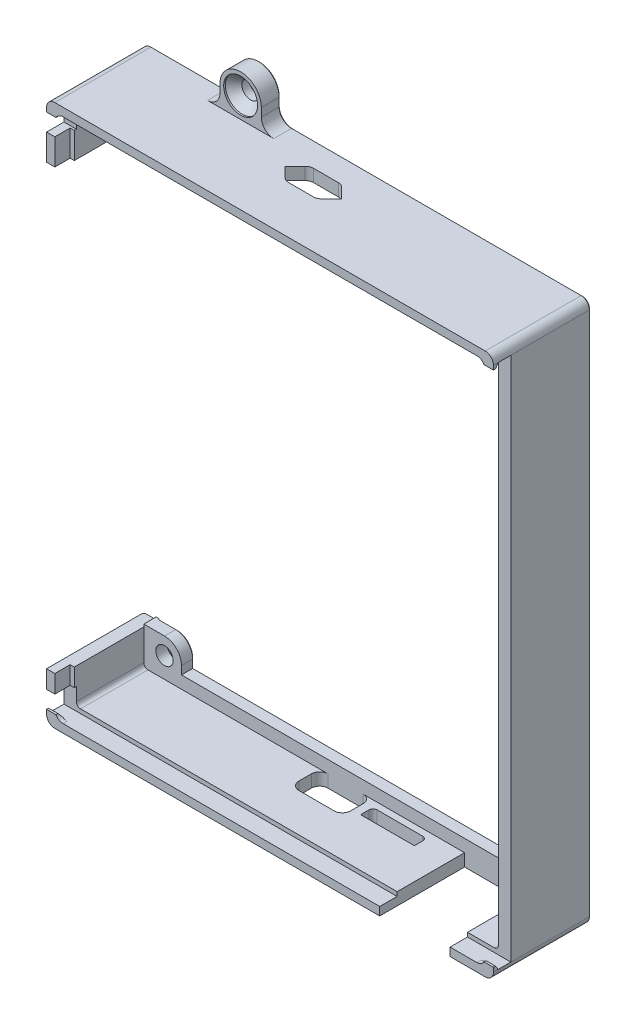
SolidWorks part; units mm, degrees
material "Custom Plastic"
ref_plane "Front Plane" through (0, 0, 0) normal (0, 0, 1) x (1, 0, 0)
ref_plane "Top Plane" through (0, 0, 0) normal (0, 1, 0) x (1, 0, 0)
ref_plane "Right Plane" through (0, 0, 0) normal (1, 0, 0) x (0, 0, -1)
sketch "Model" plane through (0, 0, 0) normal (0, 0, 1) x (1, 0, 0)
  line L0 (104.1673, 32.1811) -> (4.1672, 32.1811)
  line L1 (104.1673, 155.1806) -> (104.1673, 32.1811)
  line L2 (4.1672, 155.1806) -> (104.1673, 155.1806)
  line L3 (4.1672, 32.1811) -> (4.1672, 155.1806)
  line L4 (44.9158, 146.4259) -> (47.4224, 146.4259)
  line L5 (47.4224, 146.4259) -> (47.4224, 148.9326)
  line L6 (47.4224, 148.9326) -> (44.9158, 148.9326)
  line L7 (44.9158, 148.9326) -> (44.9158, 146.4259)
  line L8 (77.4127, 147.4278) -> (79.9193, 147.4278)
  line L9 (79.9193, 147.4278) -> (79.9193, 149.9344)
  line L10 (79.9193, 149.9344) -> (77.4127, 149.9344)
  line L11 (77.4127, 149.9344) -> (77.4127, 147.4278)
  line L12 (6.3266, 141.9721) -> (8.3592, 141.9721)
  line L13 (8.3592, 141.9721) -> (8.3592, 144.0047)
  line L14 (8.3592, 144.0047) -> (6.3266, 144.0047)
  line L15 (6.3266, 144.0047) -> (6.3266, 141.9721)
  line L16 (6.3266, 121.6529) -> (8.3592, 121.6529)
  line L17 (8.3592, 121.6529) -> (8.3592, 123.6855)
  line L18 (8.3592, 123.6855) -> (6.3266, 123.6855)
  line L19 (6.3266, 123.6855) -> (6.3266, 121.6529)
  line L20 (6.3266, 101.3324) -> (8.3592, 101.3324)
  line L21 (8.3592, 101.3324) -> (8.3592, 103.365)
  line L22 (8.3592, 103.365) -> (6.3266, 103.365)
  line L23 (6.3266, 103.365) -> (6.3266, 101.3324)
  line L24 (6.3266, 81.0118) -> (8.3592, 81.0118)
  line L25 (8.3592, 81.0118) -> (8.3592, 83.0444)
  line L26 (8.3592, 83.0444) -> (6.3266, 83.0444)
  line L27 (6.3266, 83.0444) -> (6.3266, 81.0118)
  line L28 (6.3266, 60.6927) -> (8.3592, 60.6927)
  line L29 (8.3592, 60.6927) -> (8.3592, 62.7253)
  line L30 (8.3592, 62.7253) -> (6.3266, 62.7253)
  line L31 (6.3266, 62.7253) -> (6.3266, 60.6927)
  line L32 (85.9221, 148.4144) -> (87.9547, 148.4144)
  line L33 (87.9547, 148.4144) -> (87.9547, 150.447)
  line L34 (87.9547, 150.447) -> (85.9221, 150.447)
  line L35 (85.9221, 150.447) -> (85.9221, 148.4144)
  line L36 (6.3266, 50.5324) -> (8.3592, 50.5324)
  line L37 (8.3592, 50.5324) -> (8.3592, 52.565)
  line L38 (8.3592, 52.565) -> (6.3266, 52.565)
  line L39 (6.3266, 52.565) -> (6.3266, 50.5324)
  line L40 (6.3266, 42.9118) -> (8.3592, 42.9118)
  line L41 (8.3592, 42.9118) -> (8.3592, 44.9444)
  line L42 (8.3592, 44.9444) -> (6.3266, 44.9444)
  line L43 (6.3266, 44.9444) -> (6.3266, 42.9118)
  line L44 (52.8726, 50.0418) -> (54.3815, 50.0418)
  line L45 (54.3815, 50.0418) -> (54.3815, 51.5508)
  line L46 (54.3815, 51.5508) -> (52.8726, 51.5508)
  line L47 (52.8726, 51.5508) -> (52.8726, 50.0418)
  line L48 (58.4219, 130.1637) -> (60.4545, 130.1637)
  line L49 (60.4545, 130.1637) -> (60.4545, 132.1963)
  line L50 (60.4545, 132.1963) -> (58.4219, 132.1963)
  line L51 (58.4219, 132.1963) -> (58.4219, 130.1637)
  line L52 (97.8807, 141.1439) -> (99.9133, 141.1439)
  line L53 (99.9133, 141.1439) -> (99.9133, 143.1765)
  line L54 (99.9133, 143.1765) -> (97.8807, 143.1765)
  line L55 (97.8807, 143.1765) -> (97.8807, 141.1439)
  line L56 (48.438, 37.3046) -> (48.438, 37.0552)
  line L57 (49.9456, 37.0552) -> (49.9456, 37.3046)
  line L58 (52.8877, 37.3046) -> (52.8877, 37.0552)
  line L59 (54.3967, 37.0552) -> (54.3967, 37.3046)
  line L60 (54.3126, 34.0993) -> (54.3126, 33.8995)
  line L61 (56.7201, 33.8995) -> (56.7201, 34.0993)
  line L62 (46.1133, 34.0993) -> (46.1133, 33.8995)
  line L63 (48.5207, 33.8995) -> (48.5207, 34.0993)
  line L64 (82.9607, 49.0165) -> (84.9933, 49.0165)
  line L65 (84.9933, 49.0165) -> (84.9933, 51.0492)
  line L66 (84.9933, 51.0492) -> (82.9607, 51.0492)
  line L67 (82.9607, 51.0492) -> (82.9607, 49.0165)
  line L68 (29.8828, 70.9163) -> (31.9154, 70.9163)
  line L69 (31.9154, 70.9163) -> (31.9154, 72.9489)
  line L70 (31.9154, 72.9489) -> (29.8828, 72.9489)
  line L71 (29.8828, 72.9489) -> (29.8828, 70.9163)
  line L72 (29.8828, 68.1658) -> (31.9154, 68.1658)
  line L73 (31.9154, 68.1658) -> (31.9154, 70.1984)
  line L74 (31.9154, 70.1984) -> (29.8828, 70.1984)
  line L75 (29.8828, 70.1984) -> (29.8828, 68.1658)
  line L76 (29.8828, 108.6649) -> (31.9154, 108.6649)
  line L77 (31.9154, 108.6649) -> (31.9154, 110.6975)
  line L78 (31.9154, 110.6975) -> (29.8828, 110.6975)
  line L79 (29.8828, 110.6975) -> (29.8828, 108.6649)
  line L80 (29.8828, 111.4141) -> (31.9154, 111.4141)
  line L81 (31.9154, 111.4141) -> (31.9154, 113.4467)
  line L82 (31.9154, 113.4467) -> (29.8828, 113.4467)
  line L83 (29.8828, 113.4467) -> (29.8828, 111.4141)
  line L84 (29.8828, 91.1652) -> (31.9154, 91.1652)
  line L85 (31.9154, 91.1652) -> (31.9154, 93.1978)
  line L86 (31.9154, 93.1978) -> (29.8828, 93.1978)
  line L87 (29.8828, 93.1978) -> (29.8828, 91.1652)
  line L88 (29.8828, 88.4147) -> (31.9154, 88.4147)
  line L89 (31.9154, 88.4147) -> (31.9154, 90.4473)
  line L90 (31.9154, 90.4473) -> (29.8828, 90.4473)
  line L91 (29.8828, 90.4473) -> (29.8828, 88.4147)
  line L92 (29.8828, 128.6658) -> (31.9154, 128.6658)
  line L93 (31.9154, 128.6658) -> (31.9154, 130.6984)
  line L94 (31.9154, 130.6984) -> (29.8828, 130.6984)
  line L95 (29.8828, 130.6984) -> (29.8828, 128.6658)
  line L96 (29.8828, 131.4163) -> (31.9154, 131.4163)
  line L97 (31.9154, 131.4163) -> (31.9154, 133.4489)
  line L98 (31.9154, 133.4489) -> (29.8828, 133.4489)
  line L99 (29.8828, 133.4489) -> (29.8828, 131.4163)
  line L100 (48.1611, 135.1453) -> (50.1937, 135.1453)
  line L101 (50.1937, 135.1453) -> (50.1937, 137.1779)
  line L102 (50.1937, 137.1779) -> (48.1611, 137.1779)
  line L103 (48.1611, 137.1779) -> (48.1611, 135.1453)
  line L104 (11.4074, 121.6529) -> (13.44, 121.6529)
  line L105 (13.44, 121.6529) -> (13.44, 123.6855)
  line L106 (13.44, 123.6855) -> (11.4074, 123.6855)
  line L107 (11.4074, 123.6855) -> (11.4074, 121.6529)
  line L108 (104.1673, 32.1811) -> (4.1672, 32.1811)
  line L109 (104.1673, 155.1806) -> (104.1673, 32.1811)
  line L110 (4.1672, 155.1806) -> (104.1673, 155.1806)
  line L111 (4.1672, 32.1811) -> (4.1672, 155.1806)
  spline S0 degree 3 poles (55.1711, 147.6799) (55.1711, 149.685) (52.1643, 149.685) (52.1643, 147.6799) knots 0 0 0 0 1 1 1 1
  spline S1 degree 3 poles (52.1643, 147.6799) (52.1643, 145.6749) (55.1711, 145.6749) (55.1711, 147.6799) knots 0 0 0 0 1 1 1 1
  spline S2 degree 3 poles (75.1706, 148.6804) (75.1706, 150.6854) (72.1637, 150.6854) (72.1637, 148.6804) knots 0 0 0 0 1 1 1 1
  spline S3 degree 3 poles (72.1637, 148.6804) (72.1637, 146.6754) (75.1706, 146.6754) (75.1706, 148.6804) knots 0 0 0 0 1 1 1 1
  spline S4 degree 3 poles (8.3592, 140.448) (8.3592, 141.8026) (6.3266, 141.8026) (6.3266, 140.448) knots 0 0 0 0 1 1 1 1
  spline S5 degree 3 poles (6.3266, 140.448) (6.3266, 139.0934) (8.3592, 139.0934) (8.3592, 140.448) knots 0 0 0 0 1 1 1 1
  spline S6 degree 3 poles (8.3592, 137.9083) (8.3592, 139.2629) (6.3266, 139.2629) (6.3266, 137.9083) knots 0 0 0 0 1 1 1 1
  spline S7 degree 3 poles (6.3266, 137.9083) (6.3266, 136.5537) (8.3592, 136.5537) (8.3592, 137.9083) knots 0 0 0 0 1 1 1 1
  spline S8 degree 3 poles (8.3592, 135.3686) (8.3592, 136.7232) (6.3266, 136.7232) (6.3266, 135.3686) knots 0 0 0 0 1 1 1 1
  spline S9 degree 3 poles (6.3266, 135.3686) (6.3266, 134.0139) (8.3592, 134.0139) (8.3592, 135.3686) knots 0 0 0 0 1 1 1 1
  spline S10 degree 3 poles (8.3592, 132.8288) (8.3592, 134.1834) (6.3266, 134.1834) (6.3266, 132.8288) knots 0 0 0 0 1 1 1 1
  spline S11 degree 3 poles (6.3266, 132.8288) (6.3266, 131.4742) (8.3592, 131.4742) (8.3592, 132.8288) knots 0 0 0 0 1 1 1 1
  spline S12 degree 3 poles (8.3592, 130.2891) (8.3592, 131.6437) (6.3266, 131.6437) (6.3266, 130.2891) knots 0 0 0 0 1 1 1 1
  spline S13 degree 3 poles (6.3266, 130.2891) (6.3266, 128.9331) (8.3592, 128.9331) (8.3592, 130.2891) knots 0 0 0 0 1 1 1 1
  spline S14 degree 3 poles (8.3592, 127.748) (8.3592, 129.1026) (6.3266, 129.1026) (6.3266, 127.748) knots 0 0 0 0 1 1 1 1
  spline S15 degree 3 poles (6.3266, 127.748) (6.3266, 126.3934) (8.3592, 126.3934) (8.3592, 127.748) knots 0 0 0 0 1 1 1 1
  spline S16 degree 3 poles (8.3592, 120.1288) (8.3592, 121.4834) (6.3266, 121.4834) (6.3266, 120.1288) knots 0 0 0 0 1 1 1 1
  spline S17 degree 3 poles (6.3266, 120.1288) (6.3266, 118.7742) (8.3592, 118.7742) (8.3592, 120.1288) knots 0 0 0 0 1 1 1 1
  spline S18 degree 3 poles (8.3592, 117.5891) (8.3592, 118.9437) (6.3266, 118.9437) (6.3266, 117.5891) knots 0 0 0 0 1 1 1 1
  spline S19 degree 3 poles (6.3266, 117.5891) (6.3266, 116.2331) (8.3592, 116.2331) (8.3592, 117.5891) knots 0 0 0 0 1 1 1 1
  spline S20 degree 3 poles (8.3592, 115.048) (8.3592, 116.4026) (6.3266, 116.4026) (6.3266, 115.048) knots 0 0 0 0 1 1 1 1
  spline S21 degree 3 poles (6.3266, 115.048) (6.3266, 113.6934) (8.3592, 113.6934) (8.3592, 115.048) knots 0 0 0 0 1 1 1 1
  spline S22 degree 3 poles (8.3592, 112.5083) (8.3592, 113.8629) (6.3266, 113.8629) (6.3266, 112.5083) knots 0 0 0 0 1 1 1 1
  spline S23 degree 3 poles (6.3266, 112.5083) (6.3266, 111.1537) (8.3592, 111.1537) (8.3592, 112.5083) knots 0 0 0 0 1 1 1 1
  spline S24 degree 3 poles (8.3592, 109.9686) (8.3592, 111.3232) (6.3266, 111.3232) (6.3266, 109.9686) knots 0 0 0 0 1 1 1 1
  spline S25 degree 3 poles (6.3266, 109.9686) (6.3266, 108.6139) (8.3592, 108.6139) (8.3592, 109.9686) knots 0 0 0 0 1 1 1 1
  spline S26 degree 3 poles (8.3592, 107.4288) (8.3592, 108.7834) (6.3266, 108.7834) (6.3266, 107.4288) knots 0 0 0 0 1 1 1 1
  spline S27 degree 3 poles (6.3266, 107.4288) (6.3266, 106.0742) (8.3592, 106.0742) (8.3592, 107.4288) knots 0 0 0 0 1 1 1 1
  spline S28 degree 3 poles (8.3592, 99.8083) (8.3592, 101.1629) (6.3266, 101.1629) (6.3266, 99.8083) knots 0 0 0 0 1 1 1 1
  spline S29 degree 3 poles (6.3266, 99.8083) (6.3266, 98.4537) (8.3592, 98.4537) (8.3592, 99.8083) knots 0 0 0 0 1 1 1 1
  spline S30 degree 3 poles (8.3592, 97.2686) (8.3592, 98.6232) (6.3266, 98.6232) (6.3266, 97.2686) knots 0 0 0 0 1 1 1 1
  spline S31 degree 3 poles (6.3266, 97.2686) (6.3266, 95.9139) (8.3592, 95.9139) (8.3592, 97.2686) knots 0 0 0 0 1 1 1 1
  spline S32 degree 3 poles (8.3592, 94.7288) (8.3592, 96.0834) (6.3266, 96.0834) (6.3266, 94.7288) knots 0 0 0 0 1 1 1 1
  spline S33 degree 3 poles (6.3266, 94.7288) (6.3266, 93.3742) (8.3592, 93.3742) (8.3592, 94.7288) knots 0 0 0 0 1 1 1 1
  spline S34 degree 3 poles (8.3592, 92.1891) (8.3592, 93.5437) (6.3266, 93.5437) (6.3266, 92.1891) knots 0 0 0 0 1 1 1 1
  spline S35 degree 3 poles (6.3266, 92.1891) (6.3266, 90.8331) (8.3592, 90.8331) (8.3592, 92.1891) knots 0 0 0 0 1 1 1 1
  spline S36 degree 3 poles (8.3592, 89.648) (8.3592, 91.0026) (6.3266, 91.0026) (6.3266, 89.648) knots 0 0 0 0 1 1 1 1
  spline S37 degree 3 poles (6.3266, 89.648) (6.3266, 88.2934) (8.3592, 88.2934) (8.3592, 89.648) knots 0 0 0 0 1 1 1 1
  spline S38 degree 3 poles (8.3592, 87.1083) (8.3592, 88.4629) (6.3266, 88.4629) (6.3266, 87.1083) knots 0 0 0 0 1 1 1 1
  spline S39 degree 3 poles (6.3266, 87.1083) (6.3266, 85.7537) (8.3592, 85.7537) (8.3592, 87.1083) knots 0 0 0 0 1 1 1 1
  spline S40 degree 3 poles (8.3592, 79.4891) (8.3592, 80.8437) (6.3266, 80.8437) (6.3266, 79.4891) knots 0 0 0 0 1 1 1 1
  spline S41 degree 3 poles (6.3266, 79.4891) (6.3266, 78.1331) (8.3592, 78.1331) (8.3592, 79.4891) knots 0 0 0 0 1 1 1 1
  spline S42 degree 3 poles (8.3592, 76.948) (8.3592, 78.3026) (6.3266, 78.3026) (6.3266, 76.948) knots 0 0 0 0 1 1 1 1
  spline S43 degree 3 poles (6.3266, 76.948) (6.3266, 75.5934) (8.3592, 75.5934) (8.3592, 76.948) knots 0 0 0 0 1 1 1 1
  spline S44 degree 3 poles (8.3592, 74.4083) (8.3592, 75.7629) (6.3266, 75.7629) (6.3266, 74.4083) knots 0 0 0 0 1 1 1 1
  spline S45 degree 3 poles (6.3266, 74.4083) (6.3266, 73.0537) (8.3592, 73.0537) (8.3592, 74.4083) knots 0 0 0 0 1 1 1 1
  spline S46 degree 3 poles (8.3592, 71.8685) (8.3592, 73.2232) (6.3266, 73.2232) (6.3266, 71.8685) knots 0 0 0 0 1 1 1 1
  spline S47 degree 3 poles (6.3266, 71.8685) (6.3266, 70.5139) (8.3592, 70.5139) (8.3592, 71.8685) knots 0 0 0 0 1 1 1 1
  spline S48 degree 3 poles (8.3592, 69.3288) (8.3592, 70.6834) (6.3266, 70.6834) (6.3266, 69.3288) knots 0 0 0 0 1 1 1 1
  spline S49 degree 3 poles (6.3266, 69.3288) (6.3266, 67.9742) (8.3592, 67.9742) (8.3592, 69.3288) knots 0 0 0 0 1 1 1 1
  spline S50 degree 3 poles (8.3592, 66.7891) (8.3592, 68.1437) (6.3266, 68.1437) (6.3266, 66.7891) knots 0 0 0 0 1 1 1 1
  spline S51 degree 3 poles (6.3266, 66.7891) (6.3266, 65.4331) (8.3592, 65.4331) (8.3592, 66.7891) knots 0 0 0 0 1 1 1 1
  spline S52 degree 3 poles (8.3592, 59.1686) (8.3592, 60.5232) (6.3266, 60.5232) (6.3266, 59.1686) knots 0 0 0 0 1 1 1 1
  spline S53 degree 3 poles (6.3266, 59.1686) (6.3266, 57.8139) (8.3592, 57.8139) (8.3592, 59.1686) knots 0 0 0 0 1 1 1 1
  spline S54 degree 3 poles (8.3592, 56.6288) (8.3592, 57.9834) (6.3266, 57.9834) (6.3266, 56.6288) knots 0 0 0 0 1 1 1 1
  spline S55 degree 3 poles (6.3266, 56.6288) (6.3266, 55.2742) (8.3592, 55.2742) (8.3592, 56.6288) knots 0 0 0 0 1 1 1 1
  spline S56 degree 3 poles (8.3592, 54.0891) (8.3592, 55.4437) (6.3266, 55.4437) (6.3266, 54.0891) knots 0 0 0 0 1 1 1 1
  spline S57 degree 3 poles (6.3266, 54.0891) (6.3266, 52.7331) (8.3592, 52.7331) (8.3592, 54.0891) knots 0 0 0 0 1 1 1 1
  spline S58 degree 3 poles (85.4149, 149.4301) (85.4149, 150.7847) (83.3823, 150.7847) (83.3823, 149.4301) knots 0 0 0 0 1 1 1 1
  spline S59 degree 3 poles (83.3823, 149.4301) (83.3823, 148.0754) (85.4149, 148.0754) (85.4149, 149.4301) knots 0 0 0 0 1 1 1 1
  spline S60 degree 3 poles (8.3592, 49.0083) (8.3592, 50.3629) (6.3266, 50.3629) (6.3266, 49.0083) knots 0 0 0 0 1 1 1 1
  spline S61 degree 3 poles (6.3266, 49.0083) (6.3266, 47.6537) (8.3592, 47.6537) (8.3592, 49.0083) knots 0 0 0 0 1 1 1 1
  spline S62 degree 3 poles (8.3592, 41.3891) (8.3592, 42.7437) (6.3266, 42.7437) (6.3266, 41.3891) knots 0 0 0 0 1 1 1 1
  spline S63 degree 3 poles (6.3266, 41.3891) (6.3266, 40.0331) (8.3592, 40.0331) (8.3592, 41.3891) knots 0 0 0 0 1 1 1 1
  spline S64 degree 3 poles (54.3815, 52.0661) (54.3815, 53.0721) (52.8726, 53.0721) (52.8726, 52.0661) knots 0 0 0 0 1 1 1 1
  spline S65 degree 3 poles (52.8726, 52.0661) (52.8726, 51.0602) (54.3815, 51.0602) (54.3815, 52.0661) knots 0 0 0 0 1 1 1 1
  spline S66 degree 3 poles (55.6507, 50.797) (55.6507, 51.8029) (54.1417, 51.8029) (54.1417, 50.797) knots 0 0 0 0 1 1 1 1
  spline S67 degree 3 poles (54.1417, 50.797) (54.1417, 49.791) (55.6507, 49.791) (55.6507, 50.797) knots 0 0 0 0 1 1 1 1
  spline S68 degree 3 poles (55.6507, 52.0661) (55.6507, 53.0721) (54.1417, 53.0721) (54.1417, 52.0661) knots 0 0 0 0 1 1 1 1
  spline S69 degree 3 poles (54.1417, 52.0661) (54.1417, 51.0602) (55.6507, 51.0602) (55.6507, 52.0661) knots 0 0 0 0 1 1 1 1
  spline S70 degree 3 poles (56.9212, 50.797) (56.9212, 51.8029) (55.4123, 51.8029) (55.4123, 50.797) knots 0 0 0 0 1 1 1 1
  spline S71 degree 3 poles (55.4123, 50.797) (55.4123, 49.791) (56.9212, 49.791) (56.9212, 50.797) knots 0 0 0 0 1 1 1 1
  spline S72 degree 3 poles (56.9212, 52.0661) (56.9212, 53.0721) (55.4123, 53.0721) (55.4123, 52.0661) knots 0 0 0 0 1 1 1 1
  spline S73 degree 3 poles (55.4123, 52.0661) (55.4123, 51.0602) (56.9212, 51.0602) (56.9212, 52.0661) knots 0 0 0 0 1 1 1 1
  spline S74 degree 3 poles (58.1904, 50.797) (58.1904, 51.8029) (56.6828, 51.8029) (56.6828, 50.797) knots 0 0 0 0 1 1 1 1
  spline S75 degree 3 poles (56.6828, 50.797) (56.6828, 49.791) (58.1904, 49.791) (58.1904, 50.797) knots 0 0 0 0 1 1 1 1
  spline S76 degree 3 poles (58.1904, 52.0661) (58.1904, 53.0721) (56.6828, 53.0721) (56.6828, 52.0661) knots 0 0 0 0 1 1 1 1
  spline S77 degree 3 poles (56.6828, 52.0661) (56.6828, 51.0602) (58.1904, 51.0602) (58.1904, 52.0661) knots 0 0 0 0 1 1 1 1
  spline S78 degree 3 poles (59.461, 50.797) (59.461, 51.8029) (57.952, 51.8029) (57.952, 50.797) knots 0 0 0 0 1 1 1 1
  spline S79 degree 3 poles (57.952, 50.797) (57.952, 49.791) (59.461, 49.791) (59.461, 50.797) knots 0 0 0 0 1 1 1 1
  spline S80 degree 3 poles (59.461, 52.0661) (59.461, 53.0721) (57.952, 53.0721) (57.952, 52.0661) knots 0 0 0 0 1 1 1 1
  spline S81 degree 3 poles (57.952, 52.0661) (57.952, 51.0602) (59.461, 51.0602) (59.461, 52.0661) knots 0 0 0 0 1 1 1 1
  spline S82 degree 3 poles (57.9148, 131.1793) (57.9148, 132.5353) (55.8822, 132.5353) (55.8822, 131.1793) knots 0 0 0 0 1 1 1 1
  spline S83 degree 3 poles (55.8822, 131.1793) (55.8822, 129.8247) (57.9148, 129.8247) (57.9148, 131.1793) knots 0 0 0 0 1 1 1 1
  spline S84 degree 3 poles (63.2437, 36.9311) (63.2437, 37.9371) (61.7347, 37.9371) (61.7347, 36.9311) knots 0 0 0 0 1 1 1 1
  spline S85 degree 3 poles (61.7347, 36.9311) (61.7347, 35.9252) (63.2437, 35.9252) (63.2437, 36.9311) knots 0 0 0 0 1 1 1 1
  spline S86 degree 3 poles (71.2239, 36.9311) (71.2239, 37.9371) (69.715, 37.9371) (69.715, 36.9311) knots 0 0 0 0 1 1 1 1
  spline S87 degree 3 poles (69.715, 36.9311) (69.715, 35.9252) (71.2239, 35.9252) (71.2239, 36.9311) knots 0 0 0 0 1 1 1 1
  spline S88 degree 3 poles (102.453, 142.1609) (102.453, 143.5155) (100.4204, 143.5155) (100.4204, 142.1609) knots 0 0 0 0 1 1 1 1
  spline S89 degree 3 poles (100.4204, 142.1609) (100.4204, 140.8063) (102.453, 140.8063) (102.453, 142.1609) knots 0 0 0 0 1 1 1 1
  spline S90 degree 3 poles (99.9133, 129.4609) (99.9133, 130.8155) (97.8807, 130.8155) (97.8807, 129.4609) knots 0 0 0 0 1 1 1 1
  spline S91 degree 3 poles (97.8807, 129.4609) (97.8807, 128.1063) (99.9133, 128.1063) (99.9133, 129.4609) knots 0 0 0 0 1 1 1 1
  spline S92 degree 3 poles (102.453, 139.6198) (102.453, 140.9744) (100.4204, 140.9744) (100.4204, 139.6198) knots 0 0 0 0 1 1 1 1
  spline S93 degree 3 poles (100.4204, 139.6198) (100.4204, 138.2652) (102.453, 138.2652) (102.453, 139.6198) knots 0 0 0 0 1 1 1 1
  spline S94 degree 3 poles (99.9133, 126.9198) (99.9133, 128.2744) (97.8807, 128.2744) (97.8807, 126.9198) knots 0 0 0 0 1 1 1 1
  spline S95 degree 3 poles (97.8807, 126.9198) (97.8807, 125.5652) (99.9133, 125.5652) (99.9133, 126.9198) knots 0 0 0 0 1 1 1 1
  spline S96 degree 3 poles (102.453, 137.0801) (102.453, 138.4347) (100.4204, 138.4347) (100.4204, 137.0801) knots 0 0 0 0 1 1 1 1
  spline S97 degree 3 poles (100.4204, 137.0801) (100.4204, 135.7255) (102.453, 135.7255) (102.453, 137.0801) knots 0 0 0 0 1 1 1 1
  spline S98 degree 3 poles (99.9133, 124.3801) (99.9133, 125.7347) (97.8807, 125.7347) (97.8807, 124.3801) knots 0 0 0 0 1 1 1 1
  spline S99 degree 3 poles (97.8807, 124.3801) (97.8807, 123.0255) (99.9133, 123.0255) (99.9133, 124.3801) knots 0 0 0 0 1 1 1 1
  spline S100 degree 3 poles (102.453, 134.5403) (102.453, 135.895) (100.4204, 135.895) (100.4204, 134.5403) knots 0 0 0 0 1 1 1 1
  spline S101 degree 3 poles (100.4204, 134.5403) (100.4204, 133.1857) (102.453, 133.1857) (102.453, 134.5403) knots 0 0 0 0 1 1 1 1
  spline S102 degree 3 poles (99.9133, 121.8404) (99.9133, 123.195) (97.8807, 123.195) (97.8807, 121.8404) knots 0 0 0 0 1 1 1 1
  spline S103 degree 3 poles (97.8807, 121.8404) (97.8807, 120.4857) (99.9133, 120.4857) (99.9133, 121.8404) knots 0 0 0 0 1 1 1 1
  spline S104 degree 3 poles (102.453, 132.0006) (102.453, 133.3552) (100.4204, 133.3552) (100.4204, 132.0006) knots 0 0 0 0 1 1 1 1
  spline S105 degree 3 poles (100.4204, 132.0006) (100.4204, 130.646) (102.453, 130.646) (102.453, 132.0006) knots 0 0 0 0 1 1 1 1
  spline S106 degree 3 poles (99.9133, 119.3006) (99.9133, 120.6552) (97.8807, 120.6552) (97.8807, 119.3006) knots 0 0 0 0 1 1 1 1
  spline S107 degree 3 poles (97.8807, 119.3006) (97.8807, 117.946) (99.9133, 117.946) (99.9133, 119.3006) knots 0 0 0 0 1 1 1 1
  spline S108 degree 3 poles (102.453, 129.4609) (102.453, 130.8155) (100.4204, 130.8155) (100.4204, 129.4609) knots 0 0 0 0 1 1 1 1
  spline S109 degree 3 poles (100.4204, 129.4609) (100.4204, 128.1063) (102.453, 128.1063) (102.453, 129.4609) knots 0 0 0 0 1 1 1 1
  spline S110 degree 3 poles (99.9133, 116.7609) (99.9133, 118.1155) (97.8807, 118.1155) (97.8807, 116.7609) knots 0 0 0 0 1 1 1 1
  spline S111 degree 3 poles (97.8807, 116.7609) (97.8807, 115.4063) (99.9133, 115.4063) (99.9133, 116.7609) knots 0 0 0 0 1 1 1 1
  spline S112 degree 3 poles (102.453, 126.9198) (102.453, 128.2744) (100.4204, 128.2744) (100.4204, 126.9198) knots 0 0 0 0 1 1 1 1
  spline S113 degree 3 poles (100.4204, 126.9198) (100.4204, 125.5652) (102.453, 125.5652) (102.453, 126.9198) knots 0 0 0 0 1 1 1 1
  spline S114 degree 3 poles (99.9133, 114.2198) (99.9133, 115.5744) (97.8807, 115.5744) (97.8807, 114.2198) knots 0 0 0 0 1 1 1 1
  spline S115 degree 3 poles (97.8807, 114.2198) (97.8807, 112.8652) (99.9133, 112.8652) (99.9133, 114.2198) knots 0 0 0 0 1 1 1 1
  spline S116 degree 3 poles (102.453, 124.3801) (102.453, 125.7347) (100.4204, 125.7347) (100.4204, 124.3801) knots 0 0 0 0 1 1 1 1
  spline S117 degree 3 poles (100.4204, 124.3801) (100.4204, 123.0255) (102.453, 123.0255) (102.453, 124.3801) knots 0 0 0 0 1 1 1 1
  spline S118 degree 3 poles (99.9133, 111.6801) (99.9133, 113.0347) (97.8807, 113.0347) (97.8807, 111.6801) knots 0 0 0 0 1 1 1 1
  spline S119 degree 3 poles (97.8807, 111.6801) (97.8807, 110.3255) (99.9133, 110.3255) (99.9133, 111.6801) knots 0 0 0 0 1 1 1 1
  spline S120 degree 3 poles (102.453, 121.8404) (102.453, 123.195) (100.4204, 123.195) (100.4204, 121.8404) knots 0 0 0 0 1 1 1 1
  spline S121 degree 3 poles (100.4204, 121.8404) (100.4204, 120.4857) (102.453, 120.4857) (102.453, 121.8404) knots 0 0 0 0 1 1 1 1
  spline S122 degree 3 poles (99.9133, 109.1404) (99.9133, 110.495) (97.8807, 110.495) (97.8807, 109.1404) knots 0 0 0 0 1 1 1 1
  spline S123 degree 3 poles (97.8807, 109.1404) (97.8807, 107.7857) (99.9133, 107.7857) (99.9133, 109.1404) knots 0 0 0 0 1 1 1 1
  spline S124 degree 3 poles (102.453, 119.3006) (102.453, 120.6552) (100.4204, 120.6552) (100.4204, 119.3006) knots 0 0 0 0 1 1 1 1
  spline S125 degree 3 poles (100.4204, 119.3006) (100.4204, 117.946) (102.453, 117.946) (102.453, 119.3006) knots 0 0 0 0 1 1 1 1
  spline S126 degree 3 poles (99.9133, 106.6006) (99.9133, 107.9552) (97.8807, 107.9552) (97.8807, 106.6006) knots 0 0 0 0 1 1 1 1
  spline S127 degree 3 poles (97.8807, 106.6006) (97.8807, 105.246) (99.9133, 105.246) (99.9133, 106.6006) knots 0 0 0 0 1 1 1 1
  spline S128 degree 3 poles (102.453, 116.7609) (102.453, 118.1155) (100.4204, 118.1155) (100.4204, 116.7609) knots 0 0 0 0 1 1 1 1
  spline S129 degree 3 poles (100.4204, 116.7609) (100.4204, 115.4063) (102.453, 115.4063) (102.453, 116.7609) knots 0 0 0 0 1 1 1 1
  spline S130 degree 3 poles (99.9133, 104.0609) (99.9133, 105.4155) (97.8807, 105.4155) (97.8807, 104.0609) knots 0 0 0 0 1 1 1 1
  spline S131 degree 3 poles (97.8807, 104.0609) (97.8807, 102.7063) (99.9133, 102.7063) (99.9133, 104.0609) knots 0 0 0 0 1 1 1 1
  spline S132 degree 3 poles (102.453, 114.2198) (102.453, 115.5744) (100.4204, 115.5744) (100.4204, 114.2198) knots 0 0 0 0 1 1 1 1
  spline S133 degree 3 poles (100.4204, 114.2198) (100.4204, 112.8652) (102.453, 112.8652) (102.453, 114.2198) knots 0 0 0 0 1 1 1 1
  spline S134 degree 3 poles (102.453, 111.6801) (102.453, 113.0347) (100.4204, 113.0347) (100.4204, 111.6801) knots 0 0 0 0 1 1 1 1
  spline S135 degree 3 poles (100.4204, 111.6801) (100.4204, 110.3255) (102.453, 110.3255) (102.453, 111.6801) knots 0 0 0 0 1 1 1 1
  spline S136 degree 3 poles (99.9133, 101.5198) (99.9133, 102.8744) (97.8807, 102.8744) (97.8807, 101.5198) knots 0 0 0 0 1 1 1 1
  spline S137 degree 3 poles (97.8807, 101.5198) (97.8807, 100.1652) (99.9133, 100.1652) (99.9133, 101.5198) knots 0 0 0 0 1 1 1 1
  spline S138 degree 3 poles (102.453, 109.1404) (102.453, 110.495) (100.4204, 110.495) (100.4204, 109.1404) knots 0 0 0 0 1 1 1 1
  spline S139 degree 3 poles (100.4204, 109.1404) (100.4204, 107.7857) (102.453, 107.7857) (102.453, 109.1404) knots 0 0 0 0 1 1 1 1
  spline S140 degree 3 poles (102.453, 104.0609) (102.453, 105.4155) (100.4204, 105.4155) (100.4204, 104.0609) knots 0 0 0 0 1 1 1 1
  spline S141 degree 3 poles (100.4204, 104.0609) (100.4204, 102.7063) (102.453, 102.7063) (102.453, 104.0609) knots 0 0 0 0 1 1 1 1
  spline S142 degree 3 poles (102.453, 101.5198) (102.453, 102.8744) (100.4204, 102.8744) (100.4204, 101.5198) knots 0 0 0 0 1 1 1 1
  spline S143 degree 3 poles (100.4204, 101.5198) (100.4204, 100.1652) (102.453, 100.1652) (102.453, 101.5198) knots 0 0 0 0 1 1 1 1
  spline S144 degree 3 poles (102.453, 98.9801) (102.453, 100.3347) (100.4204, 100.3347) (100.4204, 98.9801) knots 0 0 0 0 1 1 1 1
  spline S145 degree 3 poles (100.4204, 98.9801) (100.4204, 97.6255) (102.453, 97.6255) (102.453, 98.9801) knots 0 0 0 0 1 1 1 1
  spline S146 degree 3 poles (102.453, 96.4404) (102.453, 97.795) (100.4204, 97.795) (100.4204, 96.4404) knots 0 0 0 0 1 1 1 1
  spline S147 degree 3 poles (100.4204, 96.4404) (100.4204, 95.0857) (102.453, 95.0857) (102.453, 96.4404) knots 0 0 0 0 1 1 1 1
  spline S148 degree 3 poles (99.9133, 98.9801) (99.9133, 100.3347) (97.8807, 100.3347) (97.8807, 98.9801) knots 0 0 0 0 1 1 1 1
  spline S149 degree 3 poles (97.8807, 98.9801) (97.8807, 97.6255) (99.9133, 97.6255) (99.9133, 98.9801) knots 0 0 0 0 1 1 1 1
  spline S150 degree 3 poles (99.9133, 96.4404) (99.9133, 97.795) (97.8807, 97.795) (97.8807, 96.4404) knots 0 0 0 0 1 1 1 1
  spline S151 degree 3 poles (97.8807, 96.4404) (97.8807, 95.0857) (99.9133, 95.0857) (99.9133, 96.4404) knots 0 0 0 0 1 1 1 1
  spline S152 degree 3 poles (99.9133, 139.6198) (99.9133, 140.9744) (97.8807, 140.9744) (97.8807, 139.6198) knots 0 0 0 0 1 1 1 1
  spline S153 degree 3 poles (97.8807, 139.6198) (97.8807, 138.2652) (99.9133, 138.2652) (99.9133, 139.6198) knots 0 0 0 0 1 1 1 1
  spline S154 degree 3 poles (99.9133, 137.0801) (99.9133, 138.4347) (97.8807, 138.4347) (97.8807, 137.0801) knots 0 0 0 0 1 1 1 1
  spline S155 degree 3 poles (97.8807, 137.0801) (97.8807, 135.7255) (99.9133, 135.7255) (99.9133, 137.0801) knots 0 0 0 0 1 1 1 1
  spline S156 degree 3 poles (99.9133, 134.5403) (99.9133, 135.895) (97.8807, 135.895) (97.8807, 134.5403) knots 0 0 0 0 1 1 1 1
  spline S157 degree 3 poles (97.8807, 134.5403) (97.8807, 133.1857) (99.9133, 133.1857) (99.9133, 134.5403) knots 0 0 0 0 1 1 1 1
  spline S158 degree 3 poles (99.9133, 132.0006) (99.9133, 133.3552) (97.8807, 133.3552) (97.8807, 132.0006) knots 0 0 0 0 1 1 1 1
  spline S159 degree 3 poles (97.8807, 132.0006) (97.8807, 130.646) (99.9133, 130.646) (99.9133, 132.0006) knots 0 0 0 0 1 1 1 1
  spline S160 degree 3 poles (99.9133, 93.9006) (99.9133, 95.2552) (97.8807, 95.2552) (97.8807, 93.9006) knots 0 0 0 0 1 1 1 1
  spline S161 degree 3 poles (97.8807, 93.9006) (97.8807, 92.546) (99.9133, 92.546) (99.9133, 93.9006) knots 0 0 0 0 1 1 1 1
  spline S162 degree 3 poles (102.453, 93.9006) (102.453, 95.2552) (100.4204, 95.2552) (100.4204, 93.9006) knots 0 0 0 0 1 1 1 1
  spline S163 degree 3 poles (100.4204, 93.9006) (100.4204, 92.546) (102.453, 92.546) (102.453, 93.9006) knots 0 0 0 0 1 1 1 1
  spline S164 degree 3 poles (102.453, 106.6006) (102.453, 107.9552) (100.4204, 107.9552) (100.4204, 106.6006) knots 0 0 0 0 1 1 1 1
  spline S165 degree 3 poles (100.4204, 106.6006) (100.4204, 105.246) (102.453, 105.246) (102.453, 106.6006) knots 0 0 0 0 1 1 1 1
  spline S166 degree 3 poles (99.9133, 91.3609) (99.9133, 92.7155) (97.8807, 92.7155) (97.8807, 91.3609) knots 0 0 0 0 1 1 1 1
  spline S167 degree 3 poles (97.8807, 91.3609) (97.8807, 90.0063) (99.9133, 90.0063) (99.9133, 91.3609) knots 0 0 0 0 1 1 1 1
  spline S168 degree 3 poles (102.453, 91.3609) (102.453, 92.7155) (100.4204, 92.7155) (100.4204, 91.3609) knots 0 0 0 0 1 1 1 1
  spline S169 degree 3 poles (100.4204, 91.3609) (100.4204, 90.0063) (102.453, 90.0063) (102.453, 91.3609) knots 0 0 0 0 1 1 1 1
  spline S170 degree 3 poles (99.9133, 88.8198) (99.9133, 90.1744) (97.8807, 90.1744) (97.8807, 88.8198) knots 0 0 0 0 1 1 1 1
  spline S171 degree 3 poles (97.8807, 88.8198) (97.8807, 87.4652) (99.9133, 87.4652) (99.9133, 88.8198) knots 0 0 0 0 1 1 1 1
  spline S172 degree 3 poles (102.453, 88.8198) (102.453, 90.1744) (100.4204, 90.1744) (100.4204, 88.8198) knots 0 0 0 0 1 1 1 1
  spline S173 degree 3 poles (100.4204, 88.8198) (100.4204, 87.4652) (102.453, 87.4652) (102.453, 88.8198) knots 0 0 0 0 1 1 1 1
  spline S174 degree 3 poles (99.9133, 86.2801) (99.9133, 87.6347) (97.8807, 87.6347) (97.8807, 86.2801) knots 0 0 0 0 1 1 1 1
  spline S175 degree 3 poles (97.8807, 86.2801) (97.8807, 84.9255) (99.9133, 84.9255) (99.9133, 86.2801) knots 0 0 0 0 1 1 1 1
  spline S176 degree 3 poles (102.453, 86.2801) (102.453, 87.6347) (100.4204, 87.6347) (100.4204, 86.2801) knots 0 0 0 0 1 1 1 1
  spline S177 degree 3 poles (100.4204, 86.2801) (100.4204, 84.9255) (102.453, 84.9255) (102.453, 86.2801) knots 0 0 0 0 1 1 1 1
  spline S178 degree 3 poles (99.9133, 83.7404) (99.9133, 85.095) (97.8807, 85.095) (97.8807, 83.7404) knots 0 0 0 0 1 1 1 1
  spline S179 degree 3 poles (97.8807, 83.7404) (97.8807, 82.3857) (99.9133, 82.3857) (99.9133, 83.7404) knots 0 0 0 0 1 1 1 1
  spline S180 degree 3 poles (102.453, 83.7404) (102.453, 85.095) (100.4204, 85.095) (100.4204, 83.7404) knots 0 0 0 0 1 1 1 1
  spline S181 degree 3 poles (100.4204, 83.7404) (100.4204, 82.3857) (102.453, 82.3857) (102.453, 83.7404) knots 0 0 0 0 1 1 1 1
  spline S182 degree 3 poles (99.9133, 81.2006) (99.9133, 82.5552) (97.8807, 82.5552) (97.8807, 81.2006) knots 0 0 0 0 1 1 1 1
  spline S183 degree 3 poles (97.8807, 81.2006) (97.8807, 79.846) (99.9133, 79.846) (99.9133, 81.2006) knots 0 0 0 0 1 1 1 1
  spline S184 degree 3 poles (102.453, 81.2006) (102.453, 82.5552) (100.4204, 82.5552) (100.4204, 81.2006) knots 0 0 0 0 1 1 1 1
  spline S185 degree 3 poles (100.4204, 81.2006) (100.4204, 79.846) (102.453, 79.846) (102.453, 81.2006) knots 0 0 0 0 1 1 1 1
  spline S186 degree 3 poles (49.9456, 37.3046) (49.9456, 38.3106) (48.438, 38.3106) (48.438, 37.3046) knots 0 0 0 0 1 1 1 1
  spline S187 degree 3 poles (48.438, 37.0552) (48.438, 36.0492) (49.9456, 36.0492) (49.9456, 37.0552) knots 0 0 0 0 1 1 1 1
  spline S188 degree 3 poles (54.3967, 37.3046) (54.3967, 38.3106) (52.8877, 38.3106) (52.8877, 37.3046) knots 0 0 0 0 1 1 1 1
  spline S189 degree 3 poles (52.8877, 37.0552) (52.8877, 36.0492) (54.3967, 36.0492) (54.3967, 37.0552) knots 0 0 0 0 1 1 1 1
  spline S190 degree 3 poles (56.7201, 34.0993) (56.7201, 35.7047) (54.3126, 35.7047) (54.3126, 34.0993) knots 0 0 0 0 1 1 1 1
  spline S191 degree 3 poles (54.3126, 33.8995) (54.3126, 32.2941) (56.7201, 32.2941) (56.7201, 33.8995) knots 0 0 0 0 1 1 1 1
  spline S192 degree 3 poles (48.5207, 34.0993) (48.5207, 35.7047) (46.1133, 35.7047) (46.1133, 34.0993) knots 0 0 0 0 1 1 1 1
  spline S193 degree 3 poles (46.1133, 33.8995) (46.1133, 32.2941) (48.5207, 32.2941) (48.5207, 33.8995) knots 0 0 0 0 1 1 1 1
  spline S194 degree 3 poles (54.4711, 34.0001) (54.4711, 34.9054) (53.1123, 34.9054) (53.1123, 34.0001) knots 0 0 0 0 1 1 1 1
  spline S195 degree 3 poles (53.1123, 34.0001) (53.1123, 33.0933) (54.4711, 33.0933) (54.4711, 34.0001) knots 0 0 0 0 1 1 1 1
  spline S196 degree 3 poles (49.721, 34.0001) (49.721, 34.9054) (48.3623, 34.9054) (48.3623, 34.0001) knots 0 0 0 0 1 1 1 1
  spline S197 degree 3 poles (48.3623, 34.0001) (48.3623, 33.0933) (49.721, 33.0933) (49.721, 34.0001) knots 0 0 0 0 1 1 1 1
  spline S198 degree 3 poles (84.606, 43.6822) (84.606, 46.2205) (80.7985, 46.2205) (80.7985, 43.6822) knots 0 0 0 0 1 1 1 1
  spline S199 degree 3 poles (80.7985, 43.6822) (80.7985, 41.1438) (84.606, 41.1438) (84.606, 43.6822) knots 0 0 0 0 1 1 1 1
  spline S200 degree 3 poles (96.0355, 43.6822) (96.0355, 46.2205) (92.228, 46.2205) (92.228, 43.6822) knots 0 0 0 0 1 1 1 1
  spline S201 degree 3 poles (92.228, 43.6822) (92.228, 41.1438) (96.0355, 41.1438) (96.0355, 43.6822) knots 0 0 0 0 1 1 1 1
  spline S202 degree 3 poles (93.8775, 52.5719) (93.8775, 53.9265) (91.8462, 53.9265) (91.8462, 52.5719) knots 0 0 0 0 1 1 1 1
  spline S203 degree 3 poles (91.8462, 52.5719) (91.8462, 51.2173) (93.8775, 51.2173) (93.8775, 52.5719) knots 0 0 0 0 1 1 1 1
  spline S204 degree 3 poles (92.6124, 50.0322) (92.6124, 51.3868) (90.5812, 51.3868) (90.5812, 50.0322) knots 0 0 0 0 1 1 1 1
  spline S205 degree 3 poles (90.5812, 50.0322) (90.5812, 48.6775) (92.6124, 48.6775) (92.6124, 50.0322) knots 0 0 0 0 1 1 1 1
  spline S206 degree 3 poles (91.3377, 52.5719) (91.3377, 53.9265) (89.3065, 53.9265) (89.3065, 52.5719) knots 0 0 0 0 1 1 1 1
  spline S207 degree 3 poles (89.3065, 52.5719) (89.3065, 51.2173) (91.3377, 51.2173) (91.3377, 52.5719) knots 0 0 0 0 1 1 1 1
  spline S208 degree 3 poles (90.0727, 50.0322) (90.0727, 51.3868) (88.0415, 51.3868) (88.0415, 50.0322) knots 0 0 0 0 1 1 1 1
  spline S209 degree 3 poles (88.0415, 50.0322) (88.0415, 48.6775) (90.0727, 48.6775) (90.0727, 50.0322) knots 0 0 0 0 1 1 1 1
  spline S210 degree 3 poles (88.798, 52.5719) (88.798, 53.9265) (86.7654, 53.9265) (86.7654, 52.5719) knots 0 0 0 0 1 1 1 1
  spline S211 degree 3 poles (86.7654, 52.5719) (86.7654, 51.2173) (88.798, 51.2173) (88.798, 52.5719) knots 0 0 0 0 1 1 1 1
  spline S212 degree 3 poles (87.533, 50.0322) (87.533, 51.3868) (85.5018, 51.3868) (85.5018, 50.0322) knots 0 0 0 0 1 1 1 1
  spline S213 degree 3 poles (85.5018, 50.0322) (85.5018, 48.6775) (87.533, 48.6775) (87.533, 50.0322) knots 0 0 0 0 1 1 1 1
  spline S214 degree 3 poles (86.2583, 52.5719) (86.2583, 53.9265) (84.2257, 53.9265) (84.2257, 52.5719) knots 0 0 0 0 1 1 1 1
  spline S215 degree 3 poles (84.2257, 52.5719) (84.2257, 51.2173) (86.2583, 51.2173) (86.2583, 52.5719) knots 0 0 0 0 1 1 1 1
  spline S216 degree 3 poles (82.1945, 46.7331) (82.1945, 48.7644) (79.1462, 48.7644) (79.1462, 46.7331) knots 0 0 0 0 1 1 1 1
  spline S217 degree 3 poles (79.1462, 46.7331) (79.1462, 44.7005) (82.1945, 44.7005) (82.1945, 46.7331) knots 0 0 0 0 1 1 1 1
  spline S218 degree 3 poles (97.6877, 46.7304) (97.6877, 48.7616) (94.6395, 48.7616) (94.6395, 46.7304) knots 0 0 0 0 1 1 1 1
  spline S219 degree 3 poles (94.6395, 46.7304) (94.6395, 44.6978) (97.6877, 44.6978) (97.6877, 46.7304) knots 0 0 0 0 1 1 1 1
  spline S220 degree 3 poles (93.5178, 38.7819) (93.5178, 40.1365) (91.4852, 40.1365) (91.4852, 38.7819) knots 0 0 0 0 1 1 1 1
  spline S221 degree 3 poles (91.4852, 38.7819) (91.4852, 37.4272) (93.5178, 37.4272) (93.5178, 38.7819) knots 0 0 0 0 1 1 1 1
  spline S222 degree 3 poles (85.3488, 38.7819) (85.3488, 40.1365) (83.3162, 40.1365) (83.3162, 38.7819) knots 0 0 0 0 1 1 1 1
  spline S223 degree 3 poles (83.3162, 38.7819) (83.3162, 37.4272) (85.3488, 37.4272) (85.3488, 38.7819) knots 0 0 0 0 1 1 1 1
  spline S224 degree 3 poles (96.0575, 38.7819) (96.0575, 40.1365) (94.0249, 40.1365) (94.0249, 38.7819) knots 0 0 0 0 1 1 1 1
  spline S225 degree 3 poles (94.0249, 38.7819) (94.0249, 37.4272) (96.0575, 37.4272) (96.0575, 38.7819) knots 0 0 0 0 1 1 1 1
  spline S226 degree 3 poles (82.8091, 38.7819) (82.8091, 40.1365) (80.7765, 40.1365) (80.7765, 38.7819) knots 0 0 0 0 1 1 1 1
  spline S227 degree 3 poles (80.7765, 38.7819) (80.7765, 37.4272) (82.8091, 37.4272) (82.8091, 38.7819) knots 0 0 0 0 1 1 1 1
  spline S228 degree 3 poles (102.9215, 36.1815) (102.9215, 37.7029) (101.6882, 38.9362) (100.1668, 38.9362) knots 0 0 0 0 1 1 1 1
  spline S229 degree 3 poles (100.1668, 38.9362) (98.6455, 38.9362) (97.4121, 37.7028) (97.4121, 36.1815) knots 0 0 0 0 1 1 1 1
  spline S230 degree 3 poles (97.4121, 36.1815) (97.4121, 34.6601) (98.6455, 33.4268) (100.1668, 33.4268) knots 0 0 0 0 1 1 1 1
  spline S231 degree 3 poles (100.1668, 33.4268) (101.6882, 33.4268) (102.9215, 34.6601) (102.9215, 36.1815) knots 0 0 0 0 1 1 1 1
  spline S232 degree 3 poles (10.9223, 36.1815) (10.9223, 37.7028) (9.689, 38.9362) (8.1676, 38.9362) knots 0 0 0 0 1 1 1 1
  spline S233 degree 3 poles (8.1676, 38.9362) (6.6463, 38.9362) (5.4129, 37.7028) (5.4129, 36.1815) knots 0 0 0 0 1 1 1 1
  spline S234 degree 3 poles (5.4129, 36.1815) (5.4129, 34.6601) (6.6463, 33.4268) (8.1676, 33.4268) knots 0 0 0 0 1 1 1 1
  spline S235 degree 3 poles (8.1676, 33.4268) (9.689, 33.4268) (10.9223, 34.6601) (10.9223, 36.1815) knots 0 0 0 0 1 1 1 1
  spline S236 degree 3 poles (10.9223, 151.1802) (10.9223, 152.7015) (9.689, 153.9349) (8.1676, 153.9349) knots 0 0 0 0 1 1 1 1
  spline S237 degree 3 poles (8.1676, 153.9349) (6.6463, 153.9349) (5.4129, 152.7015) (5.4129, 151.1802) knots 0 0 0 0 1 1 1 1
  spline S238 degree 3 poles (5.4129, 151.1802) (5.4129, 149.6588) (6.6463, 148.4255) (8.1676, 148.4255) knots 0 0 0 0 1 1 1 1
  spline S239 degree 3 poles (8.1676, 148.4255) (9.689, 148.4255) (10.9223, 149.6588) (10.9223, 151.1802) knots 0 0 0 0 1 1 1 1
  spline S240 degree 3 poles (102.9215, 151.1802) (102.9215, 152.7015) (101.6882, 153.9349) (100.1668, 153.9349) knots 0 0 0 0 1 1 1 1
  spline S241 degree 3 poles (100.1668, 153.9349) (98.6455, 153.9349) (97.4121, 152.7015) (97.4121, 151.1802) knots 0 0 0 0 1 1 1 1
  spline S242 degree 3 poles (97.4121, 151.1802) (97.4121, 149.6588) (98.6455, 148.4255) (100.1668, 148.4255) knots 0 0 0 0 1 1 1 1
  spline S243 degree 3 poles (100.1668, 148.4255) (101.6882, 148.4255) (102.9215, 149.6588) (102.9215, 151.1802) knots 0 0 0 0 1 1 1 1
  spline S244 degree 3 poles (44.3218, 98.681) (44.3218, 99.5533) (43.0127, 99.5533) (43.0127, 98.681) knots 0 0 0 0 1 1 1 1
  spline S245 degree 3 poles (43.0127, 98.681) (43.0127, 97.8087) (44.3218, 97.8087) (44.3218, 98.681) knots 0 0 0 0 1 1 1 1
  spline S246 degree 3 poles (43.8216, 138.9322) (43.8216, 139.8045) (42.5125, 139.8045) (42.5125, 138.9322) knots 0 0 0 0 1 1 1 1
  spline S247 degree 3 poles (42.5125, 138.9322) (42.5125, 138.0599) (43.8216, 138.0599) (43.8216, 138.9322) knots 0 0 0 0 1 1 1 1
  spline S248 degree 3 poles (44.3218, 119.1807) (44.3218, 120.053) (43.0127, 120.053) (43.0127, 119.1807) knots 0 0 0 0 1 1 1 1
  spline S249 degree 3 poles (43.0127, 119.1807) (43.0127, 118.3084) (44.3218, 118.3084) (44.3218, 119.1807) knots 0 0 0 0 1 1 1 1
  spline S250 degree 3 poles (41.8221, 76.9301) (41.8221, 77.8024) (40.5143, 77.8024) (40.5143, 76.9301) knots 0 0 0 0 1 1 1 1
  spline S251 degree 3 poles (40.5143, 76.9301) (40.5143, 76.0592) (41.8221, 76.0592) (41.8221, 76.9301) knots 0 0 0 0 1 1 1 1
  spline S252 degree 3 poles (34.4551, 71.9319) (34.4551, 73.2866) (32.4225, 73.2866) (32.4225, 71.9319) knots 0 0 0 0 1 1 1 1
  spline S253 degree 3 poles (32.4225, 71.9319) (32.4225, 70.5773) (34.4551, 70.5773) (34.4551, 71.9319) knots 0 0 0 0 1 1 1 1
  spline S254 degree 3 poles (34.4551, 69.1814) (34.4551, 70.536) (32.4225, 70.536) (32.4225, 69.1814) knots 0 0 0 0 1 1 1 1
  spline S255 degree 3 poles (32.4225, 69.1814) (32.4225, 67.8268) (34.4551, 67.8268) (34.4551, 69.1814) knots 0 0 0 0 1 1 1 1
  spline S256 degree 3 poles (34.4551, 109.6819) (34.4551, 111.0365) (32.4225, 111.0365) (32.4225, 109.6819) knots 0 0 0 0 1 1 1 1
  spline S257 degree 3 poles (32.4225, 109.6819) (32.4225, 108.3273) (34.4551, 108.3273) (34.4551, 109.6819) knots 0 0 0 0 1 1 1 1
  spline S258 degree 3 poles (34.4551, 112.4297) (34.4551, 113.7843) (32.4225, 113.7843) (32.4225, 112.4297) knots 0 0 0 0 1 1 1 1
  spline S259 degree 3 poles (32.4225, 112.4297) (32.4225, 111.0751) (34.4551, 111.0751) (34.4551, 112.4297) knots 0 0 0 0 1 1 1 1
  spline S260 degree 3 poles (34.4551, 92.1808) (34.4551, 93.5354) (32.4225, 93.5354) (32.4225, 92.1808) knots 0 0 0 0 1 1 1 1
  spline S261 degree 3 poles (32.4225, 92.1808) (32.4225, 90.8262) (34.4551, 90.8262) (34.4551, 92.1808) knots 0 0 0 0 1 1 1 1
  spline S262 degree 3 poles (34.4551, 89.4303) (34.4551, 90.7849) (32.4225, 90.7849) (32.4225, 89.4303) knots 0 0 0 0 1 1 1 1
  spline S263 degree 3 poles (32.4225, 89.4303) (32.4225, 88.0757) (34.4551, 88.0757) (34.4551, 89.4303) knots 0 0 0 0 1 1 1 1
  spline S264 degree 3 poles (34.4551, 129.6814) (34.4551, 131.036) (32.4225, 131.036) (32.4225, 129.6814) knots 0 0 0 0 1 1 1 1
  spline S265 degree 3 poles (32.4225, 129.6814) (32.4225, 128.3268) (34.4551, 128.3268) (34.4551, 129.6814) knots 0 0 0 0 1 1 1 1
  spline S266 degree 3 poles (34.4551, 132.432) (34.4551, 133.7866) (32.4225, 133.7866) (32.4225, 132.432) knots 0 0 0 0 1 1 1 1
  spline S267 degree 3 poles (32.4225, 132.432) (32.4225, 131.0773) (34.4551, 131.0773) (34.4551, 132.432) knots 0 0 0 0 1 1 1 1
  spline S268 degree 3 poles (50.1923, 138.7006) (50.1923, 140.0553) (48.1611, 140.0553) (48.1611, 138.7006) knots 0 0 0 0 1 1 1 1
  spline S269 degree 3 poles (48.1611, 138.7006) (48.1611, 137.346) (50.1923, 137.346) (50.1923, 138.7006) knots 0 0 0 0 1 1 1 1
  spline S270 degree 3 poles (52.732, 136.1609) (52.732, 137.5155) (50.7008, 137.5155) (50.7008, 136.1609) knots 0 0 0 0 1 1 1 1
  spline S271 degree 3 poles (50.7008, 136.1609) (50.7008, 134.8063) (52.732, 134.8063) (52.732, 136.1609) knots 0 0 0 0 1 1 1 1
  spline S272 degree 3 poles (52.732, 138.7006) (52.732, 140.0553) (50.7008, 140.0553) (50.7008, 138.7006) knots 0 0 0 0 1 1 1 1
  spline S273 degree 3 poles (50.7008, 138.7006) (50.7008, 137.346) (52.732, 137.346) (52.732, 138.7006) knots 0 0 0 0 1 1 1 1
  spline S274 degree 3 poles (55.2731, 136.1609) (55.2731, 137.5155) (53.2405, 137.5155) (53.2405, 136.1609) knots 0 0 0 0 1 1 1 1
  spline S275 degree 3 poles (53.2405, 136.1609) (53.2405, 134.8063) (55.2731, 134.8063) (55.2731, 136.1609) knots 0 0 0 0 1 1 1 1
  spline S276 degree 3 poles (55.2731, 138.7006) (55.2731, 140.0553) (53.2405, 140.0553) (53.2405, 138.7006) knots 0 0 0 0 1 1 1 1
  spline S277 degree 3 poles (53.2405, 138.7006) (53.2405, 137.346) (55.2731, 137.346) (55.2731, 138.7006) knots 0 0 0 0 1 1 1 1
  spline S278 degree 3 poles (57.8128, 136.1609) (57.8128, 137.5155) (55.7802, 137.5155) (55.7802, 136.1609) knots 0 0 0 0 1 1 1 1
  spline S279 degree 3 poles (55.7802, 136.1609) (55.7802, 134.8063) (57.8128, 134.8063) (57.8128, 136.1609) knots 0 0 0 0 1 1 1 1
  spline S280 degree 3 poles (57.8128, 138.7006) (57.8128, 140.0553) (55.7802, 140.0553) (55.7802, 138.7006) knots 0 0 0 0 1 1 1 1
  spline S281 degree 3 poles (55.7802, 138.7006) (55.7802, 137.346) (57.8128, 137.346) (57.8128, 138.7006) knots 0 0 0 0 1 1 1 1
  spline S282 degree 3 poles (60.3526, 136.1609) (60.3526, 137.5155) (58.32, 137.5155) (58.32, 136.1609) knots 0 0 0 0 1 1 1 1
  spline S283 degree 3 poles (58.32, 136.1609) (58.32, 134.8063) (60.3526, 134.8063) (60.3526, 136.1609) knots 0 0 0 0 1 1 1 1
  spline S284 degree 3 poles (60.3526, 138.7006) (60.3526, 140.0553) (58.32, 140.0553) (58.32, 138.7006) knots 0 0 0 0 1 1 1 1
  spline S285 degree 3 poles (58.32, 138.7006) (58.32, 137.346) (60.3526, 137.346) (60.3526, 138.7006) knots 0 0 0 0 1 1 1 1
  spline S286 degree 3 poles (62.8923, 136.1609) (62.8923, 137.5155) (60.8611, 137.5155) (60.8611, 136.1609) knots 0 0 0 0 1 1 1 1
  spline S287 degree 3 poles (60.8611, 136.1609) (60.8611, 134.8063) (62.8923, 134.8063) (62.8923, 136.1609) knots 0 0 0 0 1 1 1 1
  spline S288 degree 3 poles (62.8923, 138.7006) (62.8923, 140.0553) (60.8611, 140.0553) (60.8611, 138.7006) knots 0 0 0 0 1 1 1 1
  spline S289 degree 3 poles (60.8611, 138.7006) (60.8611, 137.346) (62.8923, 137.346) (62.8923, 138.7006) knots 0 0 0 0 1 1 1 1
  spline S290 degree 3 poles (65.432, 136.1609) (65.432, 137.5155) (63.4008, 137.5155) (63.4008, 136.1609) knots 0 0 0 0 1 1 1 1
  spline S291 degree 3 poles (63.4008, 136.1609) (63.4008, 134.8063) (65.432, 134.8063) (65.432, 136.1609) knots 0 0 0 0 1 1 1 1
  spline S292 degree 3 poles (65.432, 138.7006) (65.432, 140.0553) (63.4008, 140.0553) (63.4008, 138.7006) knots 0 0 0 0 1 1 1 1
  spline S293 degree 3 poles (63.4008, 138.7006) (63.4008, 137.346) (65.432, 137.346) (65.432, 138.7006) knots 0 0 0 0 1 1 1 1
  spline S294 degree 3 poles (67.9731, 136.1609) (67.9731, 137.5155) (65.9405, 137.5155) (65.9405, 136.1609) knots 0 0 0 0 1 1 1 1
  spline S295 degree 3 poles (65.9405, 136.1609) (65.9405, 134.8063) (67.9731, 134.8063) (67.9731, 136.1609) knots 0 0 0 0 1 1 1 1
  spline S296 degree 3 poles (67.9731, 138.7006) (67.9731, 140.0553) (65.9405, 140.0553) (65.9405, 138.7006) knots 0 0 0 0 1 1 1 1
  spline S297 degree 3 poles (65.9405, 138.7006) (65.9405, 137.346) (67.9731, 137.346) (67.9731, 138.7006) knots 0 0 0 0 1 1 1 1
  spline S298 degree 3 poles (70.5128, 136.1609) (70.5128, 137.5155) (68.4802, 137.5155) (68.4802, 136.1609) knots 0 0 0 0 1 1 1 1
  spline S299 degree 3 poles (68.4802, 136.1609) (68.4802, 134.8063) (70.5128, 134.8063) (70.5128, 136.1609) knots 0 0 0 0 1 1 1 1
  spline S300 degree 3 poles (70.5128, 138.7006) (70.5128, 140.0553) (68.4802, 140.0553) (68.4802, 138.7006) knots 0 0 0 0 1 1 1 1
  spline S301 degree 3 poles (68.4802, 138.7006) (68.4802, 137.346) (70.5128, 137.346) (70.5128, 138.7006) knots 0 0 0 0 1 1 1 1
  spline S302 degree 3 poles (73.0526, 136.1609) (73.0526, 137.5155) (71.02, 137.5155) (71.02, 136.1609) knots 0 0 0 0 1 1 1 1
  spline S303 degree 3 poles (71.02, 136.1609) (71.02, 134.8063) (73.0526, 134.8063) (73.0526, 136.1609) knots 0 0 0 0 1 1 1 1
  spline S304 degree 3 poles (73.0526, 138.7006) (73.0526, 140.0553) (71.02, 140.0553) (71.02, 138.7006) knots 0 0 0 0 1 1 1 1
  spline S305 degree 3 poles (71.02, 138.7006) (71.02, 137.346) (73.0526, 137.346) (73.0526, 138.7006) knots 0 0 0 0 1 1 1 1
  spline S306 degree 3 poles (75.5923, 136.1609) (75.5923, 137.5155) (73.5611, 137.5155) (73.5611, 136.1609) knots 0 0 0 0 1 1 1 1
  spline S307 degree 3 poles (73.5611, 136.1609) (73.5611, 134.8063) (75.5923, 134.8063) (75.5923, 136.1609) knots 0 0 0 0 1 1 1 1
  spline S308 degree 3 poles (75.5923, 138.7006) (75.5923, 140.0553) (73.5611, 140.0553) (73.5611, 138.7006) knots 0 0 0 0 1 1 1 1
  spline S309 degree 3 poles (73.5611, 138.7006) (73.5611, 137.346) (75.5923, 137.346) (75.5923, 138.7006) knots 0 0 0 0 1 1 1 1
  spline S310 degree 3 poles (78.132, 136.1609) (78.132, 137.5155) (76.1008, 137.5155) (76.1008, 136.1609) knots 0 0 0 0 1 1 1 1
  spline S311 degree 3 poles (76.1008, 136.1609) (76.1008, 134.8063) (78.132, 134.8063) (78.132, 136.1609) knots 0 0 0 0 1 1 1 1
  spline S312 degree 3 poles (78.132, 138.7006) (78.132, 140.0553) (76.1008, 140.0553) (76.1008, 138.7006) knots 0 0 0 0 1 1 1 1
  spline S313 degree 3 poles (76.1008, 138.7006) (76.1008, 137.346) (78.132, 137.346) (78.132, 138.7006) knots 0 0 0 0 1 1 1 1
  spline S314 degree 3 poles (80.6731, 136.1609) (80.6731, 137.5155) (78.6405, 137.5155) (78.6405, 136.1609) knots 0 0 0 0 1 1 1 1
  spline S315 degree 3 poles (78.6405, 136.1609) (78.6405, 134.8063) (80.6731, 134.8063) (80.6731, 136.1609) knots 0 0 0 0 1 1 1 1
  spline S316 degree 3 poles (80.6731, 138.7006) (80.6731, 140.0553) (78.6405, 140.0553) (78.6405, 138.7006) knots 0 0 0 0 1 1 1 1
  spline S317 degree 3 poles (78.6405, 138.7006) (78.6405, 137.346) (80.6731, 137.346) (80.6731, 138.7006) knots 0 0 0 0 1 1 1 1
  spline S318 degree 3 poles (15.9784, 122.6685) (15.9784, 124.0232) (13.9471, 124.0232) (13.9471, 122.6685) knots 0 0 0 0 1 1 1 1
  spline S319 degree 3 poles (13.9471, 122.6685) (13.9471, 121.3139) (15.9784, 121.3139) (15.9784, 122.6685) knots 0 0 0 0 1 1 1 1
  spline S320 degree 3 poles (13.4386, 109.9686) (13.4386, 111.3232) (11.4074, 111.3232) (11.4074, 109.9686) knots 0 0 0 0 1 1 1 1
  spline S321 degree 3 poles (11.4074, 109.9686) (11.4074, 108.6139) (13.4386, 108.6139) (13.4386, 109.9686) knots 0 0 0 0 1 1 1 1
  spline S322 degree 3 poles (15.9784, 120.1288) (15.9784, 121.4834) (13.9471, 121.4834) (13.9471, 120.1288) knots 0 0 0 0 1 1 1 1
  spline S323 degree 3 poles (13.9471, 120.1288) (13.9471, 118.7742) (15.9784, 118.7742) (15.9784, 120.1288) knots 0 0 0 0 1 1 1 1
  spline S324 degree 3 poles (13.4386, 107.4288) (13.4386, 108.7834) (11.4074, 108.7834) (11.4074, 107.4288) knots 0 0 0 0 1 1 1 1
  spline S325 degree 3 poles (11.4074, 107.4288) (11.4074, 106.0742) (13.4386, 106.0742) (13.4386, 107.4288) knots 0 0 0 0 1 1 1 1
  spline S326 degree 3 poles (15.9784, 117.5891) (15.9784, 118.9437) (13.9471, 118.9437) (13.9471, 117.5891) knots 0 0 0 0 1 1 1 1
  spline S327 degree 3 poles (13.9471, 117.5891) (13.9471, 116.2331) (15.9784, 116.2331) (15.9784, 117.5891) knots 0 0 0 0 1 1 1 1
  spline S328 degree 3 poles (13.4386, 104.8891) (13.4386, 106.2437) (11.4074, 106.2437) (11.4074, 104.8891) knots 0 0 0 0 1 1 1 1
  spline S329 degree 3 poles (11.4074, 104.8891) (11.4074, 103.5331) (13.4386, 103.5331) (13.4386, 104.8891) knots 0 0 0 0 1 1 1 1
  spline S330 degree 3 poles (15.9784, 115.048) (15.9784, 116.4026) (13.9471, 116.4026) (13.9471, 115.048) knots 0 0 0 0 1 1 1 1
  spline S331 degree 3 poles (13.9471, 115.048) (13.9471, 113.6934) (15.9784, 113.6934) (15.9784, 115.048) knots 0 0 0 0 1 1 1 1
  spline S332 degree 3 poles (13.4386, 102.348) (13.4386, 103.7026) (11.4074, 103.7026) (11.4074, 102.348) knots 0 0 0 0 1 1 1 1
  spline S333 degree 3 poles (11.4074, 102.348) (11.4074, 100.9934) (13.4386, 100.9934) (13.4386, 102.348) knots 0 0 0 0 1 1 1 1
  spline S334 degree 3 poles (14.9527, 132.8288) (13.5997, 132.8958) (13.4993, 130.867) (14.8523, 130.8001) knots 0 0 0 0 1 1 1 1
  spline S335 degree 3 poles (14.8523, 130.8001) (16.2053, 130.7331) (16.3057, 132.7619) (14.9527, 132.8288) knots 0 0 0 0 1 1 1 1
  spline S336 degree 3 poles (13.4386, 99.8083) (13.4386, 101.1629) (11.4074, 101.1629) (11.4074, 99.8083) knots 0 0 0 0 1 1 1 1
  spline S337 degree 3 poles (11.4074, 99.8083) (11.4074, 98.4537) (13.4386, 98.4537) (13.4386, 99.8083) knots 0 0 0 0 1 1 1 1
  spline S338 degree 3 poles (15.9784, 109.9686) (15.9784, 111.3232) (13.9471, 111.3232) (13.9471, 109.9686) knots 0 0 0 0 1 1 1 1
  spline S339 degree 3 poles (13.9471, 109.9686) (13.9471, 108.6139) (15.9784, 108.6139) (15.9784, 109.9686) knots 0 0 0 0 1 1 1 1
  spline S340 degree 3 poles (13.4386, 97.2686) (13.4386, 98.6232) (11.4074, 98.6232) (11.4074, 97.2686) knots 0 0 0 0 1 1 1 1
  spline S341 degree 3 poles (11.4074, 97.2686) (11.4074, 95.9139) (13.4386, 95.9139) (13.4386, 97.2686) knots 0 0 0 0 1 1 1 1
  spline S342 degree 3 poles (15.9784, 107.4288) (15.9784, 108.7834) (13.9471, 108.7834) (13.9471, 107.4288) knots 0 0 0 0 1 1 1 1
  spline S343 degree 3 poles (13.9471, 107.4288) (13.9471, 106.0742) (15.9784, 106.0742) (15.9784, 107.4288) knots 0 0 0 0 1 1 1 1
  spline S344 degree 3 poles (13.4386, 94.7288) (13.4386, 96.0834) (11.4074, 96.0834) (11.4074, 94.7288) knots 0 0 0 0 1 1 1 1
  spline S345 degree 3 poles (11.4074, 94.7288) (11.4074, 93.3742) (13.4386, 93.3742) (13.4386, 94.7288) knots 0 0 0 0 1 1 1 1
  spline S346 degree 3 poles (15.9784, 104.8891) (15.9784, 106.2437) (13.9471, 106.2437) (13.9471, 104.8891) knots 0 0 0 0 1 1 1 1
  spline S347 degree 3 poles (13.9471, 104.8891) (13.9471, 103.5331) (15.9784, 103.5331) (15.9784, 104.8891) knots 0 0 0 0 1 1 1 1
  spline S348 degree 3 poles (13.4386, 92.1891) (13.4386, 93.5437) (11.4074, 93.5437) (11.4074, 92.1891) knots 0 0 0 0 1 1 1 1
  spline S349 degree 3 poles (11.4074, 92.1891) (11.4074, 90.8331) (13.4386, 90.8331) (13.4386, 92.1891) knots 0 0 0 0 1 1 1 1
  spline S350 degree 3 poles (15.9784, 102.348) (15.9784, 103.7026) (13.9471, 103.7026) (13.9471, 102.348) knots 0 0 0 0 1 1 1 1
  spline S351 degree 3 poles (13.9471, 102.348) (13.9471, 100.9934) (15.9784, 100.9934) (15.9784, 102.348) knots 0 0 0 0 1 1 1 1
  spline S352 degree 3 poles (13.4386, 89.648) (13.4386, 91.0026) (11.4074, 91.0026) (11.4074, 89.648) knots 0 0 0 0 1 1 1 1
  spline S353 degree 3 poles (11.4074, 89.648) (11.4074, 88.2934) (13.4386, 88.2934) (13.4386, 89.648) knots 0 0 0 0 1 1 1 1
  spline S354 degree 3 poles (15.9784, 99.8083) (15.9784, 101.1629) (13.9471, 101.1629) (13.9471, 99.8083) knots 0 0 0 0 1 1 1 1
  spline S355 degree 3 poles (13.9471, 99.8083) (13.9471, 98.4537) (15.9784, 98.4537) (15.9784, 99.8083) knots 0 0 0 0 1 1 1 1
  spline S356 degree 3 poles (13.4386, 87.1083) (13.4386, 88.4629) (11.4074, 88.4629) (11.4074, 87.1083) knots 0 0 0 0 1 1 1 1
  spline S357 degree 3 poles (11.4074, 87.1083) (11.4074, 85.7537) (13.4386, 85.7537) (13.4386, 87.1083) knots 0 0 0 0 1 1 1 1
  spline S358 degree 3 poles (15.9784, 97.2686) (15.9784, 98.6232) (13.9471, 98.6232) (13.9471, 97.2686) knots 0 0 0 0 1 1 1 1
  spline S359 degree 3 poles (13.9471, 97.2686) (13.9471, 95.9139) (15.9784, 95.9139) (15.9784, 97.2686) knots 0 0 0 0 1 1 1 1
  spline S360 degree 3 poles (13.4386, 84.5685) (13.4386, 85.9232) (11.4074, 85.9232) (11.4074, 84.5685) knots 0 0 0 0 1 1 1 1
  spline S361 degree 3 poles (11.4074, 84.5685) (11.4074, 83.2139) (13.4386, 83.2139) (13.4386, 84.5685) knots 0 0 0 0 1 1 1 1
  spline S362 degree 3 poles (15.9784, 94.7288) (15.9784, 96.0834) (13.9471, 96.0834) (13.9471, 94.7288) knots 0 0 0 0 1 1 1 1
  spline S363 degree 3 poles (13.9471, 94.7288) (13.9471, 93.3742) (15.9784, 93.3742) (15.9784, 94.7288) knots 0 0 0 0 1 1 1 1
  spline S364 degree 3 poles (15.9784, 92.1891) (15.9784, 93.5437) (13.9471, 93.5437) (13.9471, 92.1891) knots 0 0 0 0 1 1 1 1
  spline S365 degree 3 poles (13.9471, 92.1891) (13.9471, 90.8331) (15.9784, 90.8331) (15.9784, 92.1891) knots 0 0 0 0 1 1 1 1
  spline S366 degree 3 poles (13.4386, 82.0288) (13.4386, 83.3834) (11.4074, 83.3834) (11.4074, 82.0288) knots 0 0 0 0 1 1 1 1
  spline S367 degree 3 poles (11.4074, 82.0288) (11.4074, 80.6742) (13.4386, 80.6742) (13.4386, 82.0288) knots 0 0 0 0 1 1 1 1
  spline S368 degree 3 poles (15.9784, 89.648) (15.9784, 91.0026) (13.9471, 91.0026) (13.9471, 89.648) knots 0 0 0 0 1 1 1 1
  spline S369 degree 3 poles (13.9471, 89.648) (13.9471, 88.2934) (15.9784, 88.2934) (15.9784, 89.648) knots 0 0 0 0 1 1 1 1
  spline S370 degree 3 poles (15.9784, 84.5685) (15.9784, 85.9232) (13.9471, 85.9232) (13.9471, 84.5685) knots 0 0 0 0 1 1 1 1
  spline S371 degree 3 poles (13.9471, 84.5685) (13.9471, 83.2139) (15.9784, 83.2139) (15.9784, 84.5685) knots 0 0 0 0 1 1 1 1
  spline S372 degree 3 poles (15.9784, 82.0288) (15.9784, 83.3834) (13.9471, 83.3834) (13.9471, 82.0288) knots 0 0 0 0 1 1 1 1
  spline S373 degree 3 poles (13.9471, 82.0288) (13.9471, 80.6742) (15.9784, 80.6742) (15.9784, 82.0288) knots 0 0 0 0 1 1 1 1
  spline S374 degree 3 poles (15.9784, 79.4891) (15.9784, 80.8437) (13.9471, 80.8437) (13.9471, 79.4891) knots 0 0 0 0 1 1 1 1
  spline S375 degree 3 poles (13.9471, 79.4891) (13.9471, 78.1331) (15.9784, 78.1331) (15.9784, 79.4891) knots 0 0 0 0 1 1 1 1
  spline S376 degree 3 poles (15.9784, 76.948) (15.9784, 78.3026) (13.9471, 78.3026) (13.9471, 76.948) knots 0 0 0 0 1 1 1 1
  spline S377 degree 3 poles (13.9471, 76.948) (13.9471, 75.5934) (15.9784, 75.5934) (15.9784, 76.948) knots 0 0 0 0 1 1 1 1
  spline S378 degree 3 poles (13.4386, 79.4891) (13.4386, 80.8437) (11.4074, 80.8437) (11.4074, 79.4891) knots 0 0 0 0 1 1 1 1
  spline S379 degree 3 poles (11.4074, 79.4891) (11.4074, 78.1331) (13.4386, 78.1331) (13.4386, 79.4891) knots 0 0 0 0 1 1 1 1
  spline S380 degree 3 poles (13.4386, 76.948) (13.4386, 78.3026) (11.4074, 78.3026) (11.4074, 76.948) knots 0 0 0 0 1 1 1 1
  spline S381 degree 3 poles (11.4074, 76.948) (11.4074, 75.5934) (13.4386, 75.5934) (13.4386, 76.948) knots 0 0 0 0 1 1 1 1
  spline S382 degree 3 poles (13.4386, 120.1288) (13.4386, 121.4834) (11.4074, 121.4834) (11.4074, 120.1288) knots 0 0 0 0 1 1 1 1
  spline S383 degree 3 poles (11.4074, 120.1288) (11.4074, 118.7742) (13.4386, 118.7742) (13.4386, 120.1288) knots 0 0 0 0 1 1 1 1
  spline S384 degree 3 poles (13.4386, 117.5891) (13.4386, 118.9437) (11.4074, 118.9437) (11.4074, 117.5891) knots 0 0 0 0 1 1 1 1
  spline S385 degree 3 poles (11.4074, 117.5891) (11.4074, 116.2331) (13.4386, 116.2331) (13.4386, 117.5891) knots 0 0 0 0 1 1 1 1
  spline S386 degree 3 poles (13.4386, 115.048) (13.4386, 116.4026) (11.4074, 116.4026) (11.4074, 115.048) knots 0 0 0 0 1 1 1 1
  spline S387 degree 3 poles (11.4074, 115.048) (11.4074, 113.6934) (13.4386, 113.6934) (13.4386, 115.048) knots 0 0 0 0 1 1 1 1
  spline S388 degree 3 poles (13.4386, 112.5083) (13.4386, 113.8629) (11.4074, 113.8629) (11.4074, 112.5083) knots 0 0 0 0 1 1 1 1
  spline S389 degree 3 poles (11.4074, 112.5083) (11.4074, 111.1537) (13.4386, 111.1537) (13.4386, 112.5083) knots 0 0 0 0 1 1 1 1
  spline S390 degree 3 poles (13.4386, 74.4083) (13.4386, 75.7629) (11.4074, 75.7629) (11.4074, 74.4083) knots 0 0 0 0 1 1 1 1
  spline S391 degree 3 poles (11.4074, 74.4083) (11.4074, 73.0537) (13.4386, 73.0537) (13.4386, 74.4083) knots 0 0 0 0 1 1 1 1
  spline S392 degree 3 poles (15.9784, 74.4083) (15.9784, 75.7629) (13.9471, 75.7629) (13.9471, 74.4083) knots 0 0 0 0 1 1 1 1
  spline S393 degree 3 poles (13.9471, 74.4083) (13.9471, 73.0537) (15.9784, 73.0537) (15.9784, 74.4083) knots 0 0 0 0 1 1 1 1
  spline S394 degree 3 poles (15.9784, 87.1083) (15.9784, 88.4629) (13.9471, 88.4629) (13.9471, 87.1083) knots 0 0 0 0 1 1 1 1
  spline S395 degree 3 poles (13.9471, 87.1083) (13.9471, 85.7537) (15.9784, 85.7537) (15.9784, 87.1083) knots 0 0 0 0 1 1 1 1
  spline S396 degree 3 poles (101.1701, 42.1815) (101.1701, 43.2867) (100.2743, 44.1824) (99.1691, 44.1824) knots 0 0 0 0 1 1 1 1
  spline S397 degree 3 poles (99.1691, 44.1824) (98.064, 44.1824) (97.1669, 43.2867) (97.1669, 42.1815) knots 0 0 0 0 1 1 1 1
  spline S398 degree 3 poles (97.1669, 42.1815) (97.1669, 41.0749) (98.064, 40.1792) (99.1691, 40.1792) knots 0 0 0 0 1 1 1 1
  spline S399 degree 3 poles (99.1691, 40.1792) (100.2743, 40.1792) (101.1701, 41.0749) (101.1701, 42.1815) knots 0 0 0 0 1 1 1 1
  spline S400 degree 3 poles (56.1688, 119.1807) (56.1688, 120.2859) (55.2731, 121.183) (54.1679, 121.183) knots 0 0 0 0 1 1 1 1
  spline S401 degree 3 poles (54.1679, 121.183) (53.0627, 121.183) (52.1656, 120.2859) (52.1656, 119.1807) knots 0 0 0 0 1 1 1 1
  spline S402 degree 3 poles (52.1656, 119.1807) (52.1656, 118.0755) (53.0627, 117.1798) (54.1679, 117.1798) knots 0 0 0 0 1 1 1 1
  spline S403 degree 3 poles (54.1679, 117.1798) (55.2731, 117.1798) (56.1688, 118.0755) (56.1688, 119.1807) knots 0 0 0 0 1 1 1 1
  spline S404 degree 3 poles (16.1699, 150.1811) (16.1699, 151.2876) (15.2728, 152.1834) (14.1676, 152.1834) knots 0 0 0 0 1 1 1 1
  spline S405 degree 3 poles (14.1676, 152.1834) (13.0624, 152.1834) (12.1667, 151.2876) (12.1667, 150.1811) knots 0 0 0 0 1 1 1 1
  spline S406 degree 3 poles (12.1667, 150.1811) (12.1667, 149.0759) (13.0624, 148.1802) (14.1676, 148.1802) knots 0 0 0 0 1 1 1 1
  spline S407 degree 3 poles (14.1676, 148.1802) (15.2728, 148.1802) (16.1699, 149.0759) (16.1699, 150.1811) knots 0 0 0 0 1 1 1 1
sketch "Sketch2" plane through (0, 0, 0) normal (0, 0, 1) x (1, 0, 0)
  line L0 (0.1672, 159.1806) -> (0.1672, 28.1811)
  line L1 (4.1672, 155.1806) -> (104.1673, 155.1806) construction
  line L2 (4.1672, 155.1806) -> (4.1672, 32.1811) construction
  line L3 (4.1672, 32.1811) -> (104.1673, 32.1811) construction
  line L4 (104.1673, 155.1806) -> (104.1673, 32.1811) construction
  line L5 (0.1672, 28.1811) -> (108.1673, 28.1811)
  line L6 (108.1673, 159.1806) -> (108.1673, 28.1811)
  line L7 (0.1672, 159.1806) -> (23.1676, 159.1806)
  line L8 (104.1673, 32.1811) -> (104.1673, 28.1811) construction
  line L9 (108.1673, 32.181) -> (104.1673, 32.1811) construction
  line L10 (4.1672, 159.1806) -> (4.1672, 155.1806) construction
  line L11 (23.1676, 164.1806) -> (23.1676, 159.1806)
  line L12 (33.1676, 164.1806) -> (33.1676, 159.1806)
  line L13 (33.1676, 159.1806) -> (108.1673, 159.1806)
  line L14 (4.1672, 155.1806) -> (0.1672, 155.1806) construction
  circle A0 centre (8.1676, 151.1802) radius 2.1
  circle A1 centre (100.1668, 151.1802) radius 2.1
  circle A2 centre (100.1668, 36.1815) radius 2.1
  circle A3 centre (8.1676, 36.1815) radius 2.1
  arc A4 (33.1676, 164.1806) -> (23.1676, 164.1806) centre (28.1676, 164.1806) ccw
  circle A5 centre (28.1676, 164.1806) radius 2.1
  dimension "D2" = 5
  dimension "D3" = 20
  dimension "D4" = 4.2
  dimension "D1" = 4
extrude "Boss-Extrude1" add sketch "Sketch2" along normal blind 23.5
fillet "Fillet1" radius 2 4 edges at (0.1672, 159.1806, 11.75) (0.1672, 28.1811, 11.75) (108.1673, 28.1811, 11.75) (108.1673, 159.1806, 11.75)
sketch "Sketch5" plane through (0, 0, 23.5) normal (0, 0, 1) x (1, 0, 0)
  line L0 (3.1672, 155.1806) -> (0.1672, 155.1806) construction
  line L1 (4.1672, 156.1806) -> (104.1673, 156.1806)
  line L2 (3.1672, 155.1806) -> (3.1672, 32.181)
  line L3 (4.1672, 31.1811) -> (80.6877, 31.181)
  line L4 (105.1673, 155.1806) -> (105.1673, 32.1811)
  line L6 (4.1672, 159.1806) -> (4.1672, 156.1806) construction
  line L8 (108.1673, 32.1811) -> (105.1673, 32.1811) construction
  line L9 (108.1673, 30.181) -> (108.1673, 157.1806) construction
  line L10 (104.1673, 28.1811) -> (104.1673, 31.1811) construction
  line L12 (80.6877, 31.181) -> (80.6877, 28.1811)
  line L13 (80.6877, 28.1811) -> (97.6877, 28.1811)
  line L14 (97.6877, 28.1811) -> (97.6877, 31.181)
  line L15 (97.6877, 31.181) -> (104.1673, 31.1811)
  line L16 (0.1672, 157.1806) -> (0.1672, 30.181) construction
  line L17 (23.1676, 159.1806) -> (2.1672, 159.1806) construction
  line L18 (2.1672, 28.1811) -> (106.1673, 28.1811) construction
  arc A0 (4.1672, 156.1806) -> (3.1672, 155.1806) centre (4.1672, 155.1806) ccw
  arc A1 (105.1673, 155.1806) -> (104.1673, 156.1806) centre (104.1673, 155.1806) ccw
  arc A2 (104.1673, 31.1811) -> (105.1673, 32.1811) centre (104.1673, 32.1811) ccw
  arc A3 (3.1672, 32.181) -> (4.1672, 31.1811) centre (4.1672, 32.181) ccw
  dimension "D2" = 1
  dimension "D1" = 3
  dimension "D3" = 17
extrude "Cut-Extrude3" cut sketch "Sketch5" against normal offset from surface (20.5 mm away) 3 up to face at (102.2668, 36.1815, 0)
sketch "Sketch6" plane through (0, 0, 3) normal (0, 0, 1) x (1, 0, 0)
  line L0 (8.1676, 147.0802) -> (4.1672, 147.0802)
  line L1 (4.1672, 32.1811) -> (4.1672, 155.1806) construction
  line L3 (4.1672, 147.0802) -> (4.1672, 40.2815)
  line L4 (11.9676, 32.1811) -> (96.3668, 32.1811) construction
  line L5 (4.1672, 40.2815) -> (8.1676, 40.2815)
  line L7 (12.2676, 153.6804) -> (12.2676, 151.1802)
  line L8 (96.0668, 36.1815) -> (96.0668, 34.1813)
  line L9 (100.1668, 40.2815) -> (102.6671, 40.2815)
  line L10 (100.1668, 147.0802) -> (102.6671, 147.0802)
  line L11 (96.0668, 151.1802) -> (96.0668, 153.6804)
  line L16 (11.9676, 156.1806) -> (96.3668, 156.1806) construction
  line L17 (105.1673, 147.3802) -> (105.1673, 39.9815) construction
  line L18 (12.2676, 153.6804) -> (96.0668, 153.6804)
  line L19 (102.6671, 147.0802) -> (102.6671, 114.6808)
  line L20 (96.0668, 34.1813) -> (12.2676, 34.1813)
  line L24 (102.6671, 72.6808) -> (102.6671, 40.2815)
  line L26 (56.1673, 114.6808) -> (102.6671, 114.6808) construction
  line L28 (105.1673, 32.1811) -> (105.1673, 155.1806) construction
  line L29 (56.1673, 114.6808) -> (56.1673, 72.6808) construction
  line L30 (56.1673, 72.6808) -> (102.6671, 72.6808) construction
  line L31 (108.1673, 30.181) -> (108.1673, 157.1806) construction
  line L32 (102.6671, 114.6808) -> (102.6671, 72.6808)
  line L34 (104.1673, 32.1811) -> (4.1672, 32.1811) construction
  line L35 (12.2676, 36.1815) -> (12.2676, 34.1813)
  circle A2 centre (8.1676, 36.1815) radius 2.1 construction
  arc A9 (8.1676, 147.0802) -> (12.2676, 151.1802) centre (8.1676, 151.1802) ccw
  arc A10 (96.0668, 151.1802) -> (100.1668, 147.0802) centre (100.1668, 151.1802) ccw
  arc A12 (12.2676, 36.1815) -> (8.1676, 40.2815) centre (8.1676, 36.1815) ccw
  arc A13 (100.1668, 40.2815) -> (96.0668, 36.1815) centre (100.1668, 36.1815) ccw
  point P63 (56.1673, 93.6808)
  point P64 (108.1673, 93.6808)
  dimension "D5" = 52
  dimension "D6" = 42
extrude "Cut-Extrude4" cut sketch "Sketch6" against normal through all
sketch "Sketch7" plane through (0, 28.1811, 31.1811) normal (0, 1, 0) x (1, 0, 0)
  line L0 (4.1672, 28.181) -> (104.1673, 28.181) construction
  line L1 (45.6673, 21.181) -> (58.1673, 21.181)
  line L2 (45.6673, 21.181) -> (45.6673, 28.181)
  line L3 (45.6673, 28.181) -> (58.1673, 28.181)
  line L4 (58.1673, 21.181) -> (58.1673, 28.181)
  line L7 (60.1673, 26.581) -> (73.1673, 26.581)
  line L8 (60.1673, 26.581) -> (60.1673, 23.581)
  line L9 (60.1673, 23.581) -> (73.1673, 23.581)
  line L10 (73.1673, 26.581) -> (73.1673, 23.581)
  line L12 (105.1673, 28.181) -> (105.1673, 7.6811) construction
  line L16 (104.1673, 28.181) -> (4.1672, 28.181) construction
  dimension "D1" = 45
  dimension "D2" = 13
  dimension "D3" = 12.5
  dimension "D4" = 59.5
  dimension "D5" = 1.6
  dimension "D6" = 3
  dimension "D7" = 7
extrude "Cut-Extrude5" cut sketch "Sketch7" along normal blind 3
sketch "Sketch8" plane through (0, 0, 23.5) normal (0, 0, 1) x (1, 0, 0)
  line L0 (4.1672, 159.1806) -> (4.1672, 157.1806) construction
  line L1 (4.1672, 157.1806) -> (104.1673, 157.1806)
  line L2 (2.1672, 155.1806) -> (2.1672, 32.1811)
  line L3 (4.1672, 30.1811) -> (104.1673, 30.1811)
  line L4 (106.1673, 155.1806) -> (106.1673, 32.1811)
  line L6 (0.1672, 155.1806) -> (2.1672, 155.1806) construction
  line L8 (104.1673, 28.1811) -> (104.1673, 30.1811) construction
  line L10 (108.1673, 32.1811) -> (106.1673, 32.1811) construction
  line L11 (108.1673, 30.181) -> (108.1673, 157.1806) construction
  line L12 (0.1672, 157.1806) -> (0.1672, 30.181) construction
  line L13 (23.1676, 159.1806) -> (2.1672, 159.1806) construction
  line L14 (97.6877, 28.1811) -> (106.1673, 28.1811) construction
  arc A0 (2.1672, 155.1806) -> (4.1672, 157.1806) centre (4.1672, 155.1806) cw
  arc A1 (104.1673, 157.1806) -> (106.1673, 155.1806) centre (104.1673, 155.1806) cw
  arc A2 (106.1673, 32.1811) -> (104.1673, 30.1811) centre (104.1673, 32.1811) cw
  arc A3 (2.1672, 32.1811) -> (4.1672, 30.1811) centre (4.1672, 32.1811) ccw
  dimension "D1" = 2
  dimension "D2" = 2
extrude "Cut-Extrude6" cut sketch "Sketch8" against normal blind 3.7
fillet "Fillet3" radius 3 2 edges at (33.1676, 159.1806, 11.75) (23.1676, 159.1806, 11.75)
chamfer "Chamfer3" distance 0.3 angle 45 35 edges at (108.1673, 93.6808, 0) (0.1672, 93.6808, 0) (0.753, 28.7668, 0) (0.753, 158.5948, 0) (54.1672, 28.1811, 0) (11.1674, 159.1806, 0) (107.5815, 28.7668, 0) (10.2676, 36.1815, 0) (102.2668, 151.1802, 0) (10.2676, 151.1802, 0) (102.2668, 36.1815, 0) (12.2676, 152.4303, 0) (54.1672, 153.6804, 0) (96.0668, 152.4303, 0) (97.2677, 148.281, 0) (101.417, 147.0802, 0) (102.6671, 93.6808, 0) (101.417, 40.2815, 0) (97.2677, 39.0806, 0) (96.0668, 35.1814, 0) (54.1672, 34.1813, 0) (12.2676, 35.1814, 0) (11.0668, 39.0806, 0) (6.1674, 40.2815, 0) (4.1672, 93.6808, 0) (6.1674, 147.0802, 0) (11.0668, 148.281, 0) (71.1675, 159.1806, 0) (33.1676, 163.1806, 0) (28.1676, 169.1806, 0) (23.1676, 163.1806, 0) (30.2676, 164.1806, 0) (107.5815, 158.5948, 0) (34.0463, 160.0593, 0) (22.289, 160.0593, 0)
fillet "Fillet2" radius 2 4 edges at (45.6673, 29.681, 10) (45.6673, 29.681, 3) (58.1673, 29.681, 10) (58.1673, 29.681, 3)
sketch "Sketch9" plane through (0, 159.1806, 0) normal (0, 1, 0) x (1, 0, 0)
  line L0 (45.753, -11.4142) -> (43.3388, -9)
  line L1 (47.1672, -6) -> (53.1672, -6)
  line L2 (45.1672, -8) -> (45.1672, -10) construction
  line L3 (47.1672, -12) -> (53.1672, -12)
  line L4 (55.1672, -8) -> (55.1672, -10) construction
  line L5 (0.1672, -23.5) -> (0.1672, -0.3) construction
  line L6 (4.1672, -3) -> (104.1673, -3) construction
  line L7 (43.3388, -9) -> (45.753, -6.5858)
  line L8 (54.5814, -11.4142) -> (56.9956, -9)
  line L9 (56.9956, -9) -> (54.5814, -6.5858)
  arc A0 (53.1672, -6) -> (54.5814, -6.5858) centre (53.1672, -8) cw
  arc A1 (54.5814, -11.4142) -> (53.1672, -12) centre (53.1672, -10) cw
  arc A2 (47.1672, -12) -> (45.753, -11.4142) centre (47.1672, -10) cw
  arc A3 (45.753, -6.5858) -> (47.1672, -6) centre (47.1672, -8) cw
  dimension "D1" = 2
  dimension "D2" = 6
  dimension "D3" = 10
  dimension "D4" = 45
  dimension "D5" = 3
extrude "Cut-Extrude7" cut sketch "Sketch9" against normal up to next
sketch "Sketch10" plane through (0, 0, 23.5) normal (0, 0, 1) x (1, 0, 0)
  line L1 (17.884, 159.1806) -> (37.8444, 159.1806)
  line L2 (17.884, 159.1806) -> (17.884, 169.1806)
  line L3 (17.884, 169.1806) -> (37.8444, 169.1806)
  line L4 (37.8444, 159.1806) -> (37.8444, 169.1806)
  line L5 (20.1676, 159.1806) -> (2.1672, 159.1806) construction
  line L6 (106.1673, 159.1806) -> (36.1676, 159.1806) construction
  arc A0 (33.1676, 164.1806) -> (23.1676, 164.1806) centre (28.1676, 164.1806) ccw construction
extrude "Cut-Extrude8" cut sketch "Sketch10" against normal offset from surface (18.9 mm away) 1.6 up to face at (53.9797, 93.7433, 3)
sketch "Sketch11" plane through (0, 0, 23.5) normal (0, 0, 1) x (1, 0, 0)
  line L0 (3.1672, 39.6815) -> (3.1672, 40.2815)
  line L1 (-12.1766, 145.6802) -> (15.264, 145.6802)
  line L2 (-12.1766, 145.6802) -> (-12.1766, 39.6815)
  line L3 (-12.1766, 39.6815) -> (3.1672, 39.6815)
  line L4 (15.264, 145.6802) -> (15.264, 40.2815)
  line L6 (3.1672, 40.2815) -> (15.264, 40.2815)
  line L7 (3.1672, 32.181) -> (3.1672, 155.1806) construction
  line L8 (4.1672, 40.2815) -> (8.1676, 40.2815) construction
  point P4 (8.1676, 151.1802)
  point P5 (8.1676, 36.1815)
  dimension "D1" = 5.5
  dimension "D2" = 3.5
extrude "Cut-Extrude9" cut sketch "Sketch11" against normal through all
sketch "Sketch12" plane through (0, 0, 4.6) normal (0, 0, 1) x (1, 0, 0)
  circle A0 centre (28.1676, 164.1806) radius 4.1
  dimension "D1" = 8.2
extrude "Cut-Extrude10" cut sketch "Sketch12" against normal blind 0.4
chamfer "Chamfer4" distance 2 angle 45 1 edges at (30.2676, 164.1806, 4.2)
sketch "Sketch13" plane through (108.1673, 0, 0) normal (1, 0, 0) x (0, 0, -1)
  line L1 (-22.5, 30.181) -> (-19.3, 30.181)
  line L2 (-22.5, 30.181) -> (-22.5, 31.181)
  line L3 (-22.5, 157.1806) -> (-19.3, 157.1806)
  line L4 (-19.3, 30.181) -> (-19.3, 157.1806)
  line L8 (-23.5, 30.181) -> (-0.3, 30.181) construction
  line L9 (-0.3, 157.1806) -> (-23.5, 157.1806) construction
  line L11 (-22.5, 156.1806) -> (-23.5, 156.1806)
  line L13 (-22.5, 31.181) -> (-23.5, 31.181)
  line L14 (-23.5, 156.1806) -> (-23.5, 31.181)
  line L15 (-23.5, 30.181) -> (-23.5, 157.1806) construction
  line L16 (-22.5, 156.1806) -> (-22.5, 157.1806)
  dimension "D1" = 1
  dimension "D2" = 3.2
  dimension "D3" = 1
extrude "Cut-Extrude11" cut sketch "Sketch13" against normal up to surface (105.0001 mm away) up to face at (3.1672, 150.4304, 11.4)
sketch "Sketch14" plane through (3.1672, 0, 0) normal (1, 0, 0) x (0, 0, -1)
  line L0 (-22.5, 156.1806) -> (-23.5, 156.1806)
  line L1 (-19.3, 157.1806) -> (-22.5, 157.1806)
  line L2 (-19.3, 157.1806) -> (-19.3, 152.0045)
  line L3 (-19.3, 152.0045) -> (-22.9977, 152.0045)
  line L4 (-22.5, 157.1806) -> (-22.5, 156.1806)
  line L5 (-19.3, 30.181) -> (-22.5, 30.181)
  line L6 (-19.3, 30.181) -> (-19.3, 35.3572)
  line L7 (-19.3, 35.3572) -> (-23, 35.3572)
  line L8 (-22.5, 30.181) -> (-22.5, 31.181)
  line L9 (-23.5, 156.1806) -> (-23.5, 152.0045)
  line L10 (-23.5, 155.1806) -> (-23.5, 145.6802) construction
  line L11 (-23.5, 152.0045) -> (-22.9977, 152.0045)
  line L12 (-23.5, 30.181) -> (-23.5, 31.181) construction
  line L13 (-22.5, 31.181) -> (-23.5, 31.181)
  line L14 (-23.5, 31.181) -> (-22.5, 31.181) construction
  line L16 (-23.5, 39.6815) -> (-23.5, 32.1811) construction
  line L17 (-23.5, 35.3572) -> (-23, 35.3572)
  line L18 (-23.5, 35.3572) -> (-23.5, 31.181)
  dimension "D1" = 5.2
extrude "Cut-Extrude12" cut sketch "Sketch14" against normal through all
chamfer "Chamfer5" distance 0.7 distance2 0.5 2 edges at (1.3012, 156.1806, 22.5) (107.0333, 156.1806, 22.5) first distance on face at (1.7007, 156.7386, 22.5) first distance on face at (106.6338, 156.7386, 22.5)
fillet "Fillet4" radius 1 2 edges at (73.1673, 29.681, 4.6) (60.1673, 29.681, 4.6)
chamfer "Chamfer6" distance 0.5 distance2 0.7 2 edges at (107.0333, 31.181, 22.5) (1.3012, 31.181, 22.5) first distance on face at (107.0333, 31.181, 23) first distance on face at (1.3012, 31.181, 23)
